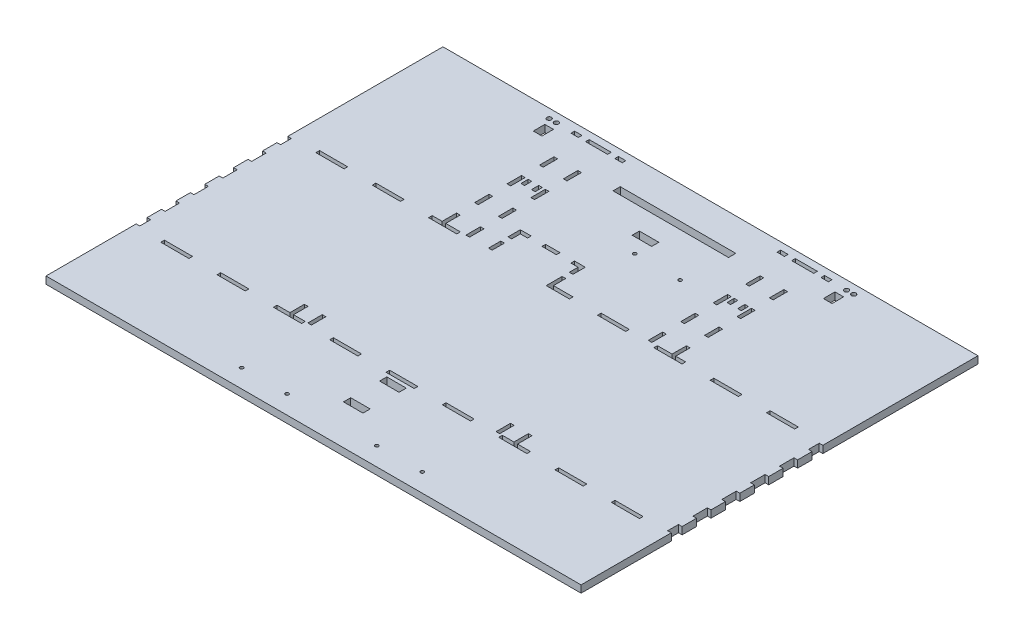
SolidWorks part; units mm, degrees
material "Acrylic (Medium-high impact)"
ref_plane "Front Plane" through (0, 0, 0) normal (0, 0, 1) x (1, 0, 0)
ref_plane "Top Plane" through (0, 0, 0) normal (0, 1, 0) x (1, 0, 0)
ref_plane "Right Plane" through (0, 0, 0) normal (1, 0, 0) x (0, 0, -1)
sketch "Sketch1" plane through (0, 0, 0) normal (0, 1, 0) x (1, 0, 0)
  line L1 (-235.3945, 69.85) -> (235.3945, 69.85)
  line L2 (-235.3945, 69.85) -> (-235.3945, -69.85)
  line L3 (-235.3945, -69.85) -> (235.3945, -69.85)
  line L4 (235.3945, 69.85) -> (235.3945, -69.85)
  point P4 (-235.3945, 0)
  point P6 (0, 69.85)
  dimension "D1" = 139.7
  dimension "D2" = 470.789
extrude "Boss-Extrude1" add sketch "Sketch1" along normal blind 6.35
sketch "Sketch2" plane through (0, 6.35, 0) normal (0, 1, 0) x (1, 0, 0)
  line L0 (235.3945, -69.85) -> (235.3945, 69.85) construction
  line L1 (-235.3945, 69.85) -> (235.3945, 69.85)
  line L2 (-235.3945, 69.85) -> (-235.3945, -69.85)
  line L3 (-235.3945, -69.85) -> (235.3945, -69.85)
  line L4 (235.3945, 69.85) -> (235.3945, -69.85)
  line L5 (-235.3945, -69.85) -> (235.3945, -69.85) construction
  line L7 (-232.2195, 66.675) -> (232.2195, 66.675)
  line L8 (-232.2195, 66.675) -> (-232.2195, -66.675)
  line L9 (-232.2195, -66.675) -> (232.2195, -66.675)
  line L10 (232.2195, 66.675) -> (232.2195, -66.675)
  point P7 (-232.2195, 0)
  point P14 (-235.3945, 0)
  point P15 (0, -66.675)
  point P16 (0, -69.85)
  point P17 (232.2195, 0)
  point P18 (235.3945, 0)
  dimension "D1" = 3.175
  dimension "D2" = 3.175
extrude "Boss-Extrude2" add sketch "Sketch2" along normal blind 298.45
sketch "Sketch3" plane through (0, 0, 69.85) normal (0, 0, 1) x (1, 0, 0)
  line L0 (73.4695, 304.8) -> (73.4695, 0) construction
  line L2 (-232.2195, 6.35) -> (232.2195, 6.35) construction
  line L4 (70.1675, 292.354) -> (70.1675, 6.35)
  line L5 (70.1675, 6.35) -> (76.7715, 6.35)
  line L6 (76.7715, 283.2407) -> (76.7715, 6.35)
  line L11 (76.7715, 101.6) -> (63.0555, 101.6) construction
  line L12 (-235.3945, 0) -> (235.3945, 0) construction
  line L13 (60.2615, 88.9) -> (60.2615, 101.6) construction
  line L14 (57.4675, 88.9) -> (63.0555, 88.9)
  line L15 (57.4675, 88.9) -> (57.4675, 71.9667)
  line L16 (57.4675, 71.9667) -> (63.0555, 71.9667)
  line L17 (63.0555, 88.9) -> (63.0555, 71.9667)
  line L18 (57.4675, 42.3333) -> (63.0555, 42.3333)
  line L19 (57.4675, 42.3333) -> (57.4675, 59.2667)
  line L20 (57.4675, 59.2667) -> (63.0555, 59.2667)
  line L21 (63.0555, 42.3333) -> (63.0555, 59.2667)
  line L26 (57.4675, 29.6333) -> (63.0555, 29.6333)
  line L27 (57.4675, 29.6333) -> (57.4675, 12.7)
  line L28 (57.4675, 12.7) -> (63.0555, 12.7)
  line L29 (63.0555, 29.6333) -> (63.0555, 12.7)
  line L30 (60.2615, 59.2667) -> (60.2615, 71.9667) construction
  line L31 (60.2615, 29.6333) -> (60.2615, 42.3333) construction
  line L32 (60.2615, 12.7) -> (60.2615, 0) construction
  line L33 (-235.3945, 304.8) -> (235.3945, 304.8) construction
  line L34 (-76.7715, 283.2407) -> (-76.7715, 6.35)
  line L35 (-76.7715, 6.35) -> (-70.1675, 6.35)
  line L36 (-70.1675, 292.354) -> (-70.1675, 6.35)
  line L37 (-70.1675, 292.354) -> (-89.7255, 292.354)
  line L38 (-79.3115, 285.7807) -> (-89.7255, 285.7807)
  line L39 (-89.7255, 292.354) -> (-89.7255, 285.7807)
  line L40 (-70.1675, 101.6) -> (-57.4675, 101.6) construction
  line L41 (-60.2615, 88.9) -> (-60.2615, 101.6) construction
  line L42 (-63.0555, 88.9) -> (-57.4675, 88.9)
  line L43 (-63.0555, 88.9) -> (-63.0555, 71.9667)
  line L44 (-63.0555, 71.9667) -> (-57.4675, 71.9667)
  line L45 (-57.4675, 88.9) -> (-57.4675, 71.9667)
  line L46 (-63.0555, 42.3333) -> (-57.4675, 42.3333)
  line L47 (-63.0555, 42.3333) -> (-63.0555, 59.2667)
  line L48 (-63.0555, 59.2667) -> (-57.4675, 59.2667)
  line L49 (-57.4675, 42.3333) -> (-57.4675, 59.2667)
  line L50 (-63.0555, 29.6333) -> (-57.4675, 29.6333)
  line L51 (-63.0555, 29.6333) -> (-63.0555, 12.7)
  line L52 (-63.0555, 12.7) -> (-57.4675, 12.7)
  line L53 (-57.4675, 29.6333) -> (-57.4675, 12.7)
  line L54 (-60.2615, 59.2667) -> (-60.2615, 71.9667) construction
  line L55 (-60.2615, 29.6333) -> (-60.2615, 42.3333) construction
  line L56 (-60.2615, 12.7) -> (-60.2615, 0) construction
  line L58 (70.1675, 292.354) -> (89.7255, 292.354)
  line L59 (89.7255, 292.354) -> (89.7255, 285.7807)
  line L60 (79.3115, 285.7807) -> (89.7255, 285.7807)
  line L61 (-235.3945, 304.8) -> (-235.3945, 0) construction
  line L62 (235.3945, 304.8) -> (235.3945, 0) construction
  arc A1 (-76.7715, 283.2407) -> (-79.3115, 285.7807) centre (-79.3115, 283.2407) ccw
  arc A2 (79.3115, 285.7807) -> (76.7715, 283.2407) centre (79.3115, 283.2407) ccw
  point P5 (73.4695, 6.35)
  dimension "D14" = 2.54
  dimension "D1" = 6.604
  dimension "D2" = 6.5733
  dimension "D3" = 158.623
  dimension "D4" = 158.623
  dimension "D6" = 101.6
  dimension "D7" = 12.7
  dimension "D8" = 12.7
  dimension "D9" = 5.588
  dimension "D11" = 6.604
  dimension "D12" = 12.954
  dimension "D13" = 286.004
  dimension "D15" = 12.7
  dimension "D16" = 12.7
  dimension "D17" = 5.588
extrude "Door Slot" cut sketch "Sketch3" against normal blind 12.7
sketch "Sketch4" plane through (0, 0, -66.675) normal (0, 0, 1) x (1, 0, 0)
  line L0 (-235.3945, 304.8) -> (235.3945, 304.8) construction
  line L1 (63.8175, 304.8) -> (70.1675, 304.8)
  line L2 (63.8175, 304.8) -> (63.8175, 6.35)
  line L3 (63.8175, 6.35) -> (70.1675, 6.35)
  line L4 (70.1675, 304.8) -> (70.1675, 6.35)
  line L5 (92.9005, 263.525) -> (92.9005, 247.65) construction
  line L7 (89.7255, 304.8) -> (96.0755, 304.8)
  line L8 (89.7255, 304.8) -> (89.7255, 6.35)
  line L9 (89.7255, 6.35) -> (96.0755, 6.35)
  line L10 (96.0755, 304.8) -> (96.0755, 6.35)
  line L11 (232.2195, 6.35) -> (-232.2195, 6.35) construction
  line L13 (70.1675, 304.8) -> (63.8175, 304.8)
  line L14 (70.1675, 304.8) -> (70.1675, 292.1)
  line L15 (70.1675, 292.1) -> (63.8175, 292.1)
  line L16 (63.8175, 304.8) -> (63.8175, 292.1)
  line L17 (70.1675, 276.225) -> (63.8175, 276.225)
  line L18 (70.1675, 276.225) -> (70.1675, 263.525)
  line L19 (70.1675, 263.525) -> (63.8175, 263.525)
  line L20 (63.8175, 276.225) -> (63.8175, 263.525)
  line L21 (63.8175, 6.35) -> (70.1675, 6.35)
  line L22 (63.8175, 6.35) -> (63.8175, 19.05)
  line L23 (63.8175, 19.05) -> (70.1675, 19.05)
  line L24 (70.1675, 6.35) -> (70.1675, 19.05)
  line L25 (63.8175, 34.925) -> (70.1675, 34.925)
  line L26 (63.8175, 34.925) -> (63.8175, 47.625)
  line L27 (63.8175, 47.625) -> (70.1675, 47.625)
  line L28 (70.1675, 34.925) -> (70.1675, 47.625)
  line L29 (63.8175, 92.075) -> (70.1675, 92.075)
  line L30 (63.8175, 92.075) -> (63.8175, 104.775)
  line L31 (63.8175, 104.775) -> (70.1675, 104.775)
  line L32 (70.1675, 92.075) -> (70.1675, 104.775)
  line L33 (63.8175, 149.225) -> (70.1675, 149.225)
  line L34 (63.8175, 149.225) -> (63.8175, 161.925)
  line L35 (63.8175, 161.925) -> (70.1675, 161.925)
  line L36 (70.1675, 149.225) -> (70.1675, 161.925)
  line L37 (63.8175, 177.8) -> (70.1675, 177.8)
  line L38 (63.8175, 177.8) -> (63.8175, 190.5)
  line L39 (63.8175, 190.5) -> (70.1675, 190.5)
  line L40 (70.1675, 177.8) -> (70.1675, 190.5)
  line L41 (63.8175, 206.375) -> (70.1675, 206.375)
  line L42 (63.8175, 206.375) -> (63.8175, 219.075)
  line L43 (63.8175, 219.075) -> (70.1675, 219.075)
  line L44 (70.1675, 206.375) -> (70.1675, 219.075)
  line L45 (63.8175, 234.95) -> (70.1675, 234.95)
  line L46 (63.8175, 234.95) -> (63.8175, 247.65)
  line L47 (63.8175, 247.65) -> (70.1675, 247.65)
  line L48 (70.1675, 234.95) -> (70.1675, 247.65)
  line L49 (70.1675, 133.35) -> (63.8175, 133.35)
  line L50 (70.1675, 133.35) -> (70.1675, 120.65)
  line L51 (70.1675, 120.65) -> (63.8175, 120.65)
  line L52 (63.8175, 133.35) -> (63.8175, 120.65)
  line L53 (70.1675, 76.2) -> (63.8175, 76.2)
  line L54 (70.1675, 76.2) -> (70.1675, 63.5)
  line L55 (70.1675, 63.5) -> (63.8175, 63.5)
  line L56 (63.8175, 76.2) -> (63.8175, 63.5)
  line L57 (66.9925, 304.8) -> (66.9925, 292.1) construction
  line L58 (66.9925, 292.1) -> (66.9925, 276.225) construction
  line L59 (66.9925, 276.225) -> (66.9925, 263.525) construction
  line L60 (66.9925, 247.65) -> (66.9925, 234.95) construction
  line L61 (66.9925, 234.95) -> (66.9925, 219.075) construction
  line L62 (66.9925, 219.075) -> (66.9925, 206.375) construction
  line L63 (66.9925, 206.375) -> (66.9925, 190.5) construction
  line L64 (66.9925, 190.5) -> (66.9925, 177.8) construction
  line L65 (66.9925, 177.8) -> (66.9925, 161.925) construction
  line L66 (66.9925, 161.925) -> (66.9925, 149.225) construction
  line L67 (66.9925, 133.35) -> (66.9925, 120.65) construction
  line L68 (66.9925, 120.65) -> (66.9925, 104.775) construction
  line L69 (66.9925, 104.775) -> (66.9925, 92.075) construction
  line L70 (66.9925, 92.075) -> (66.9925, 76.2) construction
  line L71 (66.9925, 76.2) -> (66.9925, 63.5) construction
  line L72 (66.9925, 63.5) -> (66.9925, 47.625) construction
  line L73 (66.9925, 47.625) -> (66.9925, 34.925) construction
  line L74 (66.9925, 34.925) -> (66.9925, 19.05) construction
  line L75 (66.9925, 19.05) -> (66.9925, 6.35) construction
  line L76 (66.9925, 149.225) -> (66.9925, 133.35) construction
  line L77 (66.9925, 263.525) -> (66.9925, 247.65) construction
  line L78 (79.9465, 304.8) -> (79.9465, 0) construction
  line L79 (235.3945, 304.8) -> (-235.3945, 304.8) construction
  line L80 (235.3945, 0) -> (-235.3945, 0) construction
  line L81 (79.9465, 15.1854) -> (89.7255, 15.1854) construction
  line L82 (79.9465, 15.1854) -> (70.1675, 15.1854) construction
  line L83 (92.9005, 149.225) -> (92.9005, 133.35) construction
  line L84 (92.9005, 19.05) -> (92.9005, 6.35) construction
  line L85 (92.9005, 34.925) -> (92.9005, 19.05) construction
  line L86 (92.9005, 47.625) -> (92.9005, 34.925) construction
  line L87 (92.9005, 63.5) -> (92.9005, 47.625) construction
  line L88 (92.9005, 76.2) -> (92.9005, 63.5) construction
  line L89 (92.9005, 92.075) -> (92.9005, 76.2) construction
  line L90 (92.9005, 104.775) -> (92.9005, 92.075) construction
  line L91 (92.9005, 120.65) -> (92.9005, 104.775) construction
  line L92 (92.9005, 133.35) -> (92.9005, 120.65) construction
  line L93 (92.9005, 161.925) -> (92.9005, 149.225) construction
  line L94 (92.9005, 177.8) -> (92.9005, 161.925) construction
  line L95 (92.9005, 190.5) -> (92.9005, 177.8) construction
  line L96 (92.9005, 206.375) -> (92.9005, 190.5) construction
  line L97 (92.9005, 219.075) -> (92.9005, 206.375) construction
  line L98 (92.9005, 234.95) -> (92.9005, 219.075) construction
  line L99 (92.9005, 247.65) -> (92.9005, 234.95) construction
  line L100 (92.9005, 276.225) -> (92.9005, 263.525) construction
  line L101 (92.9005, 292.1) -> (92.9005, 276.225) construction
  line L102 (92.9005, 304.8) -> (92.9005, 292.1) construction
  line L103 (96.0755, 76.2) -> (96.0755, 63.5)
  line L104 (89.7255, 63.5) -> (96.0755, 63.5)
  line L105 (89.7255, 76.2) -> (89.7255, 63.5)
  line L106 (89.7255, 76.2) -> (96.0755, 76.2)
  line L107 (96.0755, 133.35) -> (96.0755, 120.65)
  line L108 (89.7255, 120.65) -> (96.0755, 120.65)
  line L109 (89.7255, 133.35) -> (89.7255, 120.65)
  line L110 (89.7255, 133.35) -> (96.0755, 133.35)
  line L111 (89.7255, 234.95) -> (89.7255, 247.65)
  line L112 (96.0755, 247.65) -> (89.7255, 247.65)
  line L113 (96.0755, 234.95) -> (96.0755, 247.65)
  line L114 (96.0755, 234.95) -> (89.7255, 234.95)
  line L115 (89.7255, 206.375) -> (89.7255, 219.075)
  line L116 (96.0755, 219.075) -> (89.7255, 219.075)
  line L117 (96.0755, 206.375) -> (96.0755, 219.075)
  line L118 (96.0755, 206.375) -> (89.7255, 206.375)
  line L119 (89.7255, 177.8) -> (89.7255, 190.5)
  line L120 (96.0755, 190.5) -> (89.7255, 190.5)
  line L121 (96.0755, 177.8) -> (96.0755, 190.5)
  line L122 (96.0755, 177.8) -> (89.7255, 177.8)
  line L123 (89.7255, 149.225) -> (89.7255, 161.925)
  line L124 (96.0755, 161.925) -> (89.7255, 161.925)
  line L125 (96.0755, 149.225) -> (96.0755, 161.925)
  line L126 (96.0755, 149.225) -> (89.7255, 149.225)
  line L127 (89.7255, 92.075) -> (89.7255, 104.775)
  line L128 (96.0755, 104.775) -> (89.7255, 104.775)
  line L129 (96.0755, 92.075) -> (96.0755, 104.775)
  line L130 (96.0755, 92.075) -> (89.7255, 92.075)
  line L131 (89.7255, 34.925) -> (89.7255, 47.625)
  line L132 (96.0755, 47.625) -> (89.7255, 47.625)
  line L133 (96.0755, 34.925) -> (96.0755, 47.625)
  line L134 (96.0755, 34.925) -> (89.7255, 34.925)
  line L135 (89.7255, 6.35) -> (89.7255, 19.05)
  line L136 (96.0755, 19.05) -> (89.7255, 19.05)
  line L137 (96.0755, 6.35) -> (96.0755, 19.05)
  line L138 (96.0755, 6.35) -> (89.7255, 6.35)
  line L139 (96.0755, 276.225) -> (96.0755, 263.525)
  line L140 (89.7255, 263.525) -> (96.0755, 263.525)
  line L141 (89.7255, 276.225) -> (89.7255, 263.525)
  line L142 (89.7255, 276.225) -> (96.0755, 276.225)
  line L143 (96.0755, 304.8) -> (96.0755, 292.1)
  line L144 (89.7255, 292.1) -> (96.0755, 292.1)
  line L145 (89.7255, 304.8) -> (89.7255, 292.1)
  line L146 (89.7255, 304.8) -> (96.0755, 304.8)
  line L147 (89.7255, 304.8) -> (89.7255, 6.35)
  line L148 (96.0755, 6.35) -> (89.7255, 6.35)
  line L149 (96.0755, 304.8) -> (96.0755, 6.35)
  line L150 (96.0755, 304.8) -> (89.7255, 304.8)
  line L151 (-96.0755, 304.8) -> (-89.7255, 304.8)
  line L152 (-96.0755, 304.8) -> (-96.0755, 6.35)
  line L153 (-96.0755, 6.35) -> (-89.7255, 6.35)
  line L154 (-89.7255, 304.8) -> (-89.7255, 6.35)
  line L155 (-66.9925, 263.525) -> (-66.9925, 247.65) construction
  line L156 (-70.1675, 304.8) -> (-63.8175, 304.8)
  line L157 (-70.1675, 304.8) -> (-70.1675, 6.35)
  line L158 (-70.1675, 6.35) -> (-63.8175, 6.35)
  line L159 (-63.8175, 304.8) -> (-63.8175, 6.35)
  line L160 (-89.7255, 304.8) -> (-96.0755, 304.8)
  line L161 (-89.7255, 304.8) -> (-89.7255, 292.1)
  line L162 (-89.7255, 292.1) -> (-96.0755, 292.1)
  line L163 (-96.0755, 304.8) -> (-96.0755, 292.1)
  line L164 (-89.7255, 276.225) -> (-96.0755, 276.225)
  line L165 (-89.7255, 276.225) -> (-89.7255, 263.525)
  line L166 (-89.7255, 263.525) -> (-96.0755, 263.525)
  line L167 (-96.0755, 276.225) -> (-96.0755, 263.525)
  line L168 (-96.0755, 6.35) -> (-89.7255, 6.35)
  line L169 (-96.0755, 6.35) -> (-96.0755, 19.05)
  line L170 (-96.0755, 19.05) -> (-89.7255, 19.05)
  line L171 (-89.7255, 6.35) -> (-89.7255, 19.05)
  line L172 (-96.0755, 34.925) -> (-89.7255, 34.925)
  line L173 (-96.0755, 34.925) -> (-96.0755, 47.625)
  line L174 (-96.0755, 47.625) -> (-89.7255, 47.625)
  line L175 (-89.7255, 34.925) -> (-89.7255, 47.625)
  line L176 (-96.0755, 92.075) -> (-89.7255, 92.075)
  line L177 (-96.0755, 92.075) -> (-96.0755, 104.775)
  line L178 (-96.0755, 104.775) -> (-89.7255, 104.775)
  line L179 (-89.7255, 92.075) -> (-89.7255, 104.775)
  line L180 (-96.0755, 149.225) -> (-89.7255, 149.225)
  line L181 (-96.0755, 149.225) -> (-96.0755, 161.925)
  line L182 (-96.0755, 161.925) -> (-89.7255, 161.925)
  line L183 (-89.7255, 149.225) -> (-89.7255, 161.925)
  line L184 (-96.0755, 177.8) -> (-89.7255, 177.8)
  line L185 (-96.0755, 177.8) -> (-96.0755, 190.5)
  line L186 (-96.0755, 190.5) -> (-89.7255, 190.5)
  line L187 (-89.7255, 177.8) -> (-89.7255, 190.5)
  line L188 (-96.0755, 206.375) -> (-89.7255, 206.375)
  line L189 (-96.0755, 206.375) -> (-96.0755, 219.075)
  line L190 (-96.0755, 219.075) -> (-89.7255, 219.075)
  line L191 (-89.7255, 206.375) -> (-89.7255, 219.075)
  line L192 (-96.0755, 234.95) -> (-89.7255, 234.95)
  line L193 (-96.0755, 234.95) -> (-96.0755, 247.65)
  line L194 (-96.0755, 247.65) -> (-89.7255, 247.65)
  line L195 (-89.7255, 234.95) -> (-89.7255, 247.65)
  line L196 (-89.7255, 133.35) -> (-96.0755, 133.35)
  line L197 (-89.7255, 133.35) -> (-89.7255, 120.65)
  line L198 (-89.7255, 120.65) -> (-96.0755, 120.65)
  line L199 (-96.0755, 133.35) -> (-96.0755, 120.65)
  line L200 (-89.7255, 76.2) -> (-96.0755, 76.2)
  line L201 (-89.7255, 76.2) -> (-89.7255, 63.5)
  line L202 (-89.7255, 63.5) -> (-96.0755, 63.5)
  line L203 (-96.0755, 76.2) -> (-96.0755, 63.5)
  line L204 (-92.9005, 304.8) -> (-92.9005, 292.1) construction
  line L205 (-92.9005, 292.1) -> (-92.9005, 276.225) construction
  line L206 (-92.9005, 276.225) -> (-92.9005, 263.525) construction
  line L207 (-92.9005, 247.65) -> (-92.9005, 234.95) construction
  line L208 (-92.9005, 234.95) -> (-92.9005, 219.075) construction
  line L209 (-92.9005, 219.075) -> (-92.9005, 206.375) construction
  line L210 (-92.9005, 206.375) -> (-92.9005, 190.5) construction
  line L211 (-92.9005, 190.5) -> (-92.9005, 177.8) construction
  line L212 (-92.9005, 177.8) -> (-92.9005, 161.925) construction
  line L213 (-92.9005, 161.925) -> (-92.9005, 149.225) construction
  line L214 (-92.9005, 133.35) -> (-92.9005, 120.65) construction
  line L215 (-92.9005, 120.65) -> (-92.9005, 104.775) construction
  line L216 (-92.9005, 104.775) -> (-92.9005, 92.075) construction
  line L217 (-92.9005, 92.075) -> (-92.9005, 76.2) construction
  line L218 (-92.9005, 76.2) -> (-92.9005, 63.5) construction
  line L219 (-92.9005, 63.5) -> (-92.9005, 47.625) construction
  line L220 (-92.9005, 47.625) -> (-92.9005, 34.925) construction
  line L221 (-92.9005, 34.925) -> (-92.9005, 19.05) construction
  line L222 (-92.9005, 19.05) -> (-92.9005, 6.35) construction
  line L223 (-92.9005, 149.225) -> (-92.9005, 133.35) construction
  line L224 (-92.9005, 263.525) -> (-92.9005, 247.65) construction
  line L225 (-79.9465, 304.8) -> (-79.9465, 0) construction
  line L226 (-79.9465, 341.727) -> (-70.1675, 341.727) construction
  line L227 (-79.9465, 341.727) -> (-89.7255, 341.727) construction
  line L228 (-66.9925, 149.225) -> (-66.9925, 133.35) construction
  line L229 (-66.9925, 19.05) -> (-66.9925, 6.35) construction
  line L230 (-66.9925, 34.925) -> (-66.9925, 19.05) construction
  line L231 (-66.9925, 47.625) -> (-66.9925, 34.925) construction
  line L232 (-66.9925, 63.5) -> (-66.9925, 47.625) construction
  line L233 (-66.9925, 76.2) -> (-66.9925, 63.5) construction
  line L234 (-66.9925, 92.075) -> (-66.9925, 76.2) construction
  line L235 (-66.9925, 104.775) -> (-66.9925, 92.075) construction
  line L236 (-66.9925, 120.65) -> (-66.9925, 104.775) construction
  line L237 (-66.9925, 133.35) -> (-66.9925, 120.65) construction
  line L238 (-66.9925, 161.925) -> (-66.9925, 149.225) construction
  line L239 (-66.9925, 177.8) -> (-66.9925, 161.925) construction
  line L240 (-66.9925, 190.5) -> (-66.9925, 177.8) construction
  line L241 (-66.9925, 206.375) -> (-66.9925, 190.5) construction
  line L242 (-66.9925, 219.075) -> (-66.9925, 206.375) construction
  line L243 (-66.9925, 234.95) -> (-66.9925, 219.075) construction
  line L244 (-66.9925, 247.65) -> (-66.9925, 234.95) construction
  line L245 (-66.9925, 276.225) -> (-66.9925, 263.525) construction
  line L246 (-66.9925, 292.1) -> (-66.9925, 276.225) construction
  line L247 (-66.9925, 304.8) -> (-66.9925, 292.1) construction
  line L248 (-63.8175, 76.2) -> (-63.8175, 63.5)
  line L249 (-70.1675, 63.5) -> (-63.8175, 63.5)
  line L250 (-70.1675, 76.2) -> (-70.1675, 63.5)
  line L251 (-70.1675, 76.2) -> (-63.8175, 76.2)
  line L252 (-63.8175, 133.35) -> (-63.8175, 120.65)
  line L253 (-70.1675, 120.65) -> (-63.8175, 120.65)
  line L254 (-70.1675, 133.35) -> (-70.1675, 120.65)
  line L255 (-70.1675, 133.35) -> (-63.8175, 133.35)
  line L256 (-70.1675, 234.95) -> (-70.1675, 247.65)
  line L257 (-63.8175, 247.65) -> (-70.1675, 247.65)
  line L258 (-63.8175, 234.95) -> (-63.8175, 247.65)
  line L259 (-63.8175, 234.95) -> (-70.1675, 234.95)
  line L260 (-70.1675, 206.375) -> (-70.1675, 219.075)
  line L261 (-63.8175, 219.075) -> (-70.1675, 219.075)
  line L262 (-63.8175, 206.375) -> (-63.8175, 219.075)
  line L263 (-63.8175, 206.375) -> (-70.1675, 206.375)
  line L264 (-70.1675, 177.8) -> (-70.1675, 190.5)
  line L265 (-63.8175, 190.5) -> (-70.1675, 190.5)
  line L266 (-63.8175, 177.8) -> (-63.8175, 190.5)
  line L267 (-63.8175, 177.8) -> (-70.1675, 177.8)
  line L268 (-70.1675, 149.225) -> (-70.1675, 161.925)
  line L269 (-63.8175, 161.925) -> (-70.1675, 161.925)
  line L270 (-63.8175, 149.225) -> (-63.8175, 161.925)
  line L271 (-63.8175, 149.225) -> (-70.1675, 149.225)
  line L272 (-70.1675, 92.075) -> (-70.1675, 104.775)
  line L273 (-63.8175, 104.775) -> (-70.1675, 104.775)
  line L274 (-63.8175, 92.075) -> (-63.8175, 104.775)
  line L275 (-63.8175, 92.075) -> (-70.1675, 92.075)
  line L276 (-70.1675, 34.925) -> (-70.1675, 47.625)
  line L277 (-63.8175, 47.625) -> (-70.1675, 47.625)
  line L278 (-63.8175, 34.925) -> (-63.8175, 47.625)
  line L279 (-63.8175, 34.925) -> (-70.1675, 34.925)
  line L280 (-70.1675, 6.35) -> (-70.1675, 19.05)
  line L281 (-63.8175, 19.05) -> (-70.1675, 19.05)
  line L282 (-63.8175, 6.35) -> (-63.8175, 19.05)
  line L283 (-63.8175, 6.35) -> (-70.1675, 6.35)
  line L284 (-63.8175, 276.225) -> (-63.8175, 263.525)
  line L285 (-70.1675, 263.525) -> (-63.8175, 263.525)
  line L286 (-70.1675, 276.225) -> (-70.1675, 263.525)
  line L287 (-70.1675, 276.225) -> (-63.8175, 276.225)
  line L288 (-63.8175, 304.8) -> (-63.8175, 292.1)
  line L289 (-70.1675, 292.1) -> (-63.8175, 292.1)
  line L290 (-70.1675, 304.8) -> (-70.1675, 292.1)
  line L291 (-70.1675, 304.8) -> (-63.8175, 304.8)
  line L292 (-70.1675, 304.8) -> (-70.1675, 6.35)
  line L293 (-63.8175, 6.35) -> (-70.1675, 6.35)
  line L294 (-63.8175, 304.8) -> (-63.8175, 6.35)
  line L295 (-63.8175, 304.8) -> (-70.1675, 304.8)
  line L296 (-235.3945, 0) -> (235.3945, 0) construction
  line L297 (-89.7255, 292.354) -> (-89.7255, 285.7807) construction
  line L298 (-70.1675, 6.35) -> (-70.1675, 292.354) construction
  line L299 (70.1675, 292.354) -> (70.1675, 6.35) construction
  line L300 (89.7255, 285.7807) -> (89.7255, 292.354) construction
  dimension "D1" = 6.35
  dimension "D2" = 12.7
  dimension "D3" = 6.35
  dimension "D4" = 12.7
extrude "Door Guide Holes" cut sketch "Sketch4" against normal up to next (3.175 mm away) contours L2 L47 L4 L19 | L45 L2 L43 L4 | L41 L2 L39 L4 | L37 L2 L35 L4 | L49 L4 L33 L2 | L4 L51 L2 L31 | L53 L4 L29 L2 | L4 L55 L2 L27 | L25 L2 L23 L4 | L164 L154 L162 L152 | L152 L194 L154 L166 | L192 L152 L190 L154 | L188 L152 L186 L154 | L184 L152 L182 L154 | L196 L154 L180 L152 | L154 L198 L152 L178 | L200 L154 L176 L152 | L154 L202 L152 L174 | L172 L152 L170 L154 | L144 L8 L142 L10 | L140 L8 L112 L10 | L116 L10 L114 L8 | L120 L10 L118 L8 | L124 L10 L122 L8 | L10 L126 L8 L110 | L128 L10 L108 L8 | L10 L130 L8 L106 | L132 L10 L104 L8 | L136 L10 L134 L8 | L289 L157 L287 L159 | L285 L157 L257 L159 | L261 L159 L259 L157 | L265 L159 L263 L157 | L269 L159 L267 L157 | L159 L271 L157 L255 | L273 L159 L253 L157 | L159 L275 L157 L251 | L277 L159 L249 L157 | L281 L159 L279 L157 | L17 L4 L15 L2 region at (66.9925, 284.1625, -66.675) region at (66.9925, 255.5875, -66.675) region at (66.9925, 227.0125, -66.675) region at (66.9925, 198.4375, -66.675) region at (66.9925, 169.8625, -66.675) region at (66.9925, 141.2875, -66.675) region at (66.9925, 112.7125, -66.675) region at (66.9925, 84.1375, -66.675) region at (66.9925, 55.5625, -66.675) region at (66.9925, 26.9875, -66.675) region at (92.9005, 284.1625, -66.675) region at (92.9005, 255.5875, -66.675) region at (92.9005, 227.0125, -66.675) region at (92.9005, 198.4375, -66.675) region at (92.9005, 169.8625, -66.675) region at (92.9005, 141.2875, -66.675) region at (92.9005, 112.7125, -66.675) region at (92.9005, 84.1375, -66.675) region at (92.9005, 55.5625, -66.675) region at (92.9005, 26.9875, -66.675) region at (-92.9005, 284.1625, -66.675) region at (-92.9005, 255.5875, -66.675) region at (-92.9005, 227.0125, -66.675) region at (-92.9005, 198.4375, -66.675) region at (-92.9005, 169.8625, -66.675) region at (-92.9005, 141.2875, -66.675) region at (-92.9005, 112.7125, -66.675) region at (-92.9005, 84.1375, -66.675) region at (-92.9005, 55.5625, -66.675) region at (-92.9005, 26.9875, -66.675) region at (-66.9925, 284.1625, -66.675) region at (-66.9925, 255.5875, -66.675) region at (-66.9925, 227.0125, -66.675) region at (-66.9925, 198.4375, -66.675) region at (-66.9925, 169.8625, -66.675) region at (-66.9925, 141.2875, -66.675) region at (-66.9925, 112.7125, -66.675) region at (-66.9925, 84.1375, -66.675) region at (-66.9925, 55.5625, -66.675) region at (-66.9925, 26.9875, -66.675)
sketch "Lever Holes" plane through (0, 0, -69.85) normal (0, 0, 1) x (1, 0, 0)
  line L0 (-53.2675, 37.685) -> (-27.8675, 37.685)
  line L1 (-53.2675, 37.685) -> (-53.2675, 30.065)
  line L2 (-53.2675, 30.065) -> (-27.8675, 30.065)
  line L3 (-27.8675, 37.685) -> (-27.8675, 30.065)
  line L4 (-53.8175, 16.35) -> (-49.8175, 16.35)
  line L5 (-53.8175, 16.35) -> (-53.8175, 10)
  line L6 (-53.8175, 10) -> (-49.8175, 10)
  line L7 (-49.8175, 16.35) -> (-49.8175, 10)
  line L8 (-7.8175, 16.35) -> (-3.8175, 16.35)
  line L9 (-7.8175, 16.35) -> (-7.8175, 10)
  line L10 (-7.8175, 10) -> (-3.8175, 10)
  line L11 (-3.8175, 16.35) -> (-3.8175, 10)
  line L12 (-49.8175, 13.175) -> (-7.8175, 13.175) construction
  line L13 (76.7715, 6.35) -> (76.7715, 283.2407) construction
  line L14 (76.7715, 6.35) -> (232.2195, 6.35) construction
  line L15 (232.2195, 6.35) -> (-232.2195, 6.35) construction
  line L16 (216.3445, 160.275) -> (216.3445, 144.525) construction
  line L17 (235.3945, 304.8) -> (235.3945, 0) construction
  line L18 (0, -3.4925) -> (0, 3.4925) construction
  line L19 (76.7715, 154.6735) -> (-76.7715, 154.6735) construction
  line L20 (-76.7715, 283.2407) -> (-76.7715, 6.35) construction
  line L21 (0, 171.6172) -> (0, 142.0428) construction
  line L22 (7.8175, 16.35) -> (7.8175, 10)
  line L23 (7.8175, 10) -> (3.8175, 10)
  line L24 (3.8175, 16.35) -> (3.8175, 10)
  line L25 (7.8175, 16.35) -> (3.8175, 16.35)
  line L26 (53.2675, 37.685) -> (53.2675, 30.065)
  line L27 (53.2675, 30.065) -> (27.8675, 30.065)
  line L28 (27.8675, 37.685) -> (27.8675, 30.065)
  line L29 (53.2675, 37.685) -> (27.8675, 37.685)
  line L30 (53.8175, 16.35) -> (53.8175, 10)
  line L31 (53.8175, 10) -> (49.8175, 10)
  line L32 (49.8175, 16.35) -> (49.8175, 10)
  line L33 (53.8175, 16.35) -> (49.8175, 16.35)
  line L35 (63.8175, 19.05) -> (63.8175, 34.925) construction
  circle A0 centre (216.3445, 160.275) radius 1.5
  circle A1 centre (216.3445, 144.525) radius 1.5
  circle A2 centre (-216.3445, 160.275) radius 1.5
  circle A3 centre (-216.3445, 144.525) radius 1.5
  point P13 (-40.5675, 30.065)
  point P31 (216.3445, 152.4)
  point P32 (235.3945, 152.4)
  dimension "D10" = 3
  dimension "D1" = 25.4
  dimension "D2" = 7.62
  dimension "D3" = 4
  dimension "D4" = 6.35
  dimension "D5" = 42
  dimension "D6" = 31.335
  dimension "D7" = 10
  dimension "D8" = 10
  dimension "D9" = 13.25
  dimension "D11" = 15.75
  dimension "D12" = 19.05
extrude "LeverHole Cut" cut sketch "Lever Holes" along normal up to next
extrude "Lbracket Thru Holes" cut sketch "Lever Holes<2>" along normal through all contours A2 | A3 | A0 | A1 | A2 | A3 | A0 | A1 region at (216.3445, 160.275, -69.85) region at (216.3445, 144.525, -69.85) region at (-216.3445, 160.275, -69.85) region at (-216.3445, 144.525, -69.85)
sketch "Lever Holes<2>" plane through (0, 0, -69.85) normal (0, 0, 1) x (1, 0, 0) same geometry as "Lever Holes"
sketch "Sketch8" plane through (-235.3945, 0, 0) normal (-1, 0, 0) x (0, 0, 1)
  line L0 (-69.85, 0) -> (69.85, 0) construction
  circle A0 centre (0, 19.05) radius 3.175
  point P6 (0, 0)
  dimension "D1" = 6.35
  dimension "D2" = 19.05
extrude "Tether Hole" cut sketch "Sketch8" against normal through all
sketch "Sketch16" plane through (0, 0, 69.85) normal (0, 0, 1) x (1, 0, 0)
  line L0 (-235.3945, 304.8) -> (235.3945, 304.8) construction
  line L1 (57.3405, 304.8) -> (102.5525, 304.8)
  line L2 (57.3405, 304.8) -> (57.3405, 295.529)
  line L3 (57.3405, 295.529) -> (102.5525, 295.529)
  line L4 (102.5525, 304.8) -> (102.5525, 295.529)
  line L6 (47.8155, 295.529) -> (57.3405, 295.529)
  line L8 (57.3405, 295.529) -> (57.3405, 304.8)
  line L9 (57.3405, 304.8) -> (47.8155, 304.8)
  line L10 (47.8155, 295.529) -> (47.8155, 304.8)
  line L11 (102.5525, 295.529) -> (112.0775, 295.529)
  line L12 (102.5525, 295.529) -> (102.5525, 304.8)
  line L13 (102.5525, 304.8) -> (112.0775, 304.8)
  line L14 (112.0775, 295.529) -> (112.0775, 304.8)
  line L15 (89.7255, 292.354) -> (70.1675, 292.354) construction
  line L16 (-102.5525, 304.8) -> (-57.3405, 304.8)
  line L17 (-102.5525, 304.8) -> (-102.5525, 295.529)
  line L18 (-102.5525, 295.529) -> (-57.3405, 295.529)
  line L19 (-57.3405, 304.8) -> (-57.3405, 295.529)
  line L20 (-112.0775, 295.529) -> (-102.5525, 295.529)
  line L21 (-102.5525, 295.529) -> (-102.5525, 304.8)
  line L22 (-102.5525, 304.8) -> (-112.0775, 304.8)
  line L23 (-112.0775, 295.529) -> (-112.0775, 304.8)
  line L24 (-57.3405, 295.529) -> (-47.8155, 295.529)
  line L25 (-57.3405, 295.529) -> (-57.3405, 304.8)
  line L26 (-57.3405, 304.8) -> (-47.8155, 304.8)
  line L27 (-47.8155, 295.529) -> (-47.8155, 304.8)
  line L28 (-70.1675, 292.354) -> (-89.7255, 292.354) construction
  point P15 (79.9465, 292.354)
  point P16 (79.9465, 295.529)
  point P25 (-79.9465, 292.354)
  point P28 (-79.9465, 295.529)
  dimension "D1" = 45.212
  dimension "D2" = 3.175
  dimension "D3" = 9.525
  dimension "D4" = 45.212
  dimension "D5" = 9.525
extrude "Door Guide Roof Slots" cut sketch "Sketch16" against normal up to next contours L10 L6 L2 L9 | L11 L14 L13 L4 | L23 L20 L17 L22 | L24 L27 L26 L19 region at (52.578, 300.1645, 69.85) region at (107.315, 300.1645, 69.85) region at (-107.315, 300.1645, 69.85) region at (-52.578, 300.1645, 69.85)
sketch "Bottom" plane through (0, 0, 0) normal (0, -1, 0) x (1, 0, 0)
  line L0 (-232.2195, 66.675) -> (-112.0775, 66.675) construction
  line L1 (-235.3945, 69.85) -> (-210.6161, 69.85)
  line L2 (-235.3945, 69.85) -> (-235.3945, 66.675)
  line L3 (-235.3945, 66.675) -> (-210.6161, 66.675)
  line L4 (-210.6161, 69.85) -> (-210.6161, 66.675)
  line L5 (-210.6161, 69.85) -> (-185.8378, 69.85)
  line L6 (-210.6161, 69.85) -> (-210.6161, 66.675)
  line L7 (-210.6161, 66.675) -> (-185.8378, 66.675)
  line L8 (-185.8378, 69.85) -> (-185.8378, 66.675)
  line L9 (-185.8378, 69.85) -> (-161.0594, 69.85)
  line L10 (-185.8378, 69.85) -> (-185.8378, 66.675)
  line L11 (-185.8378, 66.675) -> (-161.0594, 66.675)
  line L12 (-161.0594, 69.85) -> (-161.0594, 66.675)
  line L13 (-161.0594, 69.85) -> (-136.281, 69.85)
  line L14 (-161.0594, 69.85) -> (-161.0594, 66.675)
  line L15 (-161.0594, 66.675) -> (-136.281, 66.675)
  line L16 (-136.281, 69.85) -> (-136.281, 66.675)
  line L17 (-235.3945, 69.85) -> (235.3945, 69.85) construction
  line L19 (-136.281, 69.85) -> (-111.5027, 69.85)
  line L20 (-136.281, 69.85) -> (-136.281, 66.675)
  line L21 (-136.281, 66.675) -> (-111.5027, 66.675)
  line L22 (-111.5027, 69.85) -> (-111.5027, 66.675)
  line L23 (-111.5027, 69.85) -> (-86.7243, 69.85)
  line L24 (-111.5027, 69.85) -> (-111.5027, 66.675)
  line L25 (-111.5027, 66.675) -> (-86.7243, 66.675)
  line L26 (-86.7243, 69.85) -> (-86.7243, 66.675)
  line L27 (-86.7243, 69.85) -> (-61.9459, 69.85)
  line L28 (-86.7243, 69.85) -> (-86.7243, 66.675)
  line L29 (-86.7243, 66.675) -> (-61.9459, 66.675)
  line L30 (-61.9459, 69.85) -> (-61.9459, 66.675)
  line L31 (-61.9459, 69.85) -> (-37.1676, 69.85)
  line L32 (-61.9459, 69.85) -> (-61.9459, 66.675)
  line L33 (-61.9459, 66.675) -> (-37.1676, 66.675)
  line L34 (-37.1676, 69.85) -> (-37.1676, 66.675)
  line L36 (-37.1676, 69.85) -> (-12.3892, 69.85)
  line L37 (-37.1676, 69.85) -> (-37.1676, 66.675)
  line L38 (-37.1676, 66.675) -> (-12.3892, 66.675)
  line L39 (-12.3892, 69.85) -> (-12.3892, 66.675)
  line L40 (-12.3892, 69.85) -> (12.3892, 69.85)
  line L41 (-12.3892, 69.85) -> (-12.3892, 66.675)
  line L42 (-12.3892, 66.675) -> (12.3892, 66.675)
  line L43 (12.3892, 69.85) -> (12.3892, 66.675)
  line L44 (12.3892, 69.85) -> (37.1676, 69.85)
  line L45 (12.3892, 69.85) -> (12.3892, 66.675)
  line L46 (12.3892, 66.675) -> (37.1676, 66.675)
  line L47 (37.1676, 69.85) -> (37.1676, 66.675)
  line L48 (37.1676, 69.85) -> (61.9459, 69.85)
  line L49 (37.1676, 69.85) -> (37.1676, 66.675)
  line L50 (37.1676, 66.675) -> (61.9459, 66.675)
  line L51 (61.9459, 69.85) -> (61.9459, 66.675)
  line L52 (61.9459, 69.85) -> (86.7243, 69.85)
  line L53 (61.9459, 69.85) -> (61.9459, 66.675)
  line L54 (61.9459, 66.675) -> (86.7243, 66.675)
  line L55 (86.7243, 69.85) -> (86.7243, 66.675)
  line L56 (86.7243, 69.85) -> (111.5027, 69.85)
  line L57 (86.7243, 69.85) -> (86.7243, 66.675)
  line L58 (86.7243, 66.675) -> (111.5027, 66.675)
  line L59 (111.5027, 69.85) -> (111.5027, 66.675)
  line L60 (111.5027, 69.85) -> (136.281, 69.85)
  line L61 (111.5027, 69.85) -> (111.5027, 66.675)
  line L62 (111.5027, 66.675) -> (136.281, 66.675)
  line L63 (136.281, 69.85) -> (136.281, 66.675)
  line L64 (136.281, 69.85) -> (161.0594, 69.85)
  line L65 (136.281, 69.85) -> (136.281, 66.675)
  line L66 (136.281, 66.675) -> (161.0594, 66.675)
  line L67 (161.0594, 69.85) -> (161.0594, 66.675)
  line L68 (161.0594, 69.85) -> (185.8378, 69.85)
  line L69 (161.0594, 69.85) -> (161.0594, 66.675)
  line L70 (161.0594, 66.675) -> (185.8378, 66.675)
  line L71 (185.8378, 69.85) -> (185.8378, 66.675)
  line L72 (185.8378, 69.85) -> (210.6161, 69.85)
  line L73 (185.8378, 69.85) -> (185.8378, 66.675)
  line L74 (185.8378, 66.675) -> (210.6161, 66.675)
  line L75 (210.6161, 69.85) -> (210.6161, 66.675)
  line L76 (-232.2195, -66.675) -> (-232.2195, 66.675) construction
  line L77 (-235.3945, 69.85) -> (-232.2195, 69.85)
  line L78 (-235.3945, 69.85) -> (-235.3945, 57.15)
  line L79 (-235.3945, 57.15) -> (-232.2195, 57.15)
  line L80 (-232.2195, 69.85) -> (-232.2195, 57.15)
  line L82 (-235.3945, 57.15) -> (-232.2195, 57.15)
  line L83 (-235.3945, 57.15) -> (-235.3945, 44.45)
  line L84 (-235.3945, 44.45) -> (-232.2195, 44.45)
  line L85 (-232.2195, 57.15) -> (-232.2195, 44.45)
  line L86 (-235.3945, 44.45) -> (-232.2195, 44.45)
  line L87 (-235.3945, 44.45) -> (-235.3945, 31.75)
  line L88 (-235.3945, 31.75) -> (-232.2195, 31.75)
  line L89 (-232.2195, 44.45) -> (-232.2195, 31.75)
  line L90 (-235.3945, 31.75) -> (-232.2195, 31.75)
  line L91 (-235.3945, 31.75) -> (-235.3945, 19.05)
  line L92 (-235.3945, 19.05) -> (-232.2195, 19.05)
  line L93 (-232.2195, 31.75) -> (-232.2195, 19.05)
  line L94 (-235.3945, 19.05) -> (-232.2195, 19.05)
  line L95 (-235.3945, 19.05) -> (-235.3945, 6.35)
  line L96 (-235.3945, 6.35) -> (-232.2195, 6.35)
  line L97 (-232.2195, 19.05) -> (-232.2195, 6.35)
  line L98 (-235.3945, 6.35) -> (-232.2195, 6.35)
  line L99 (-235.3945, 6.35) -> (-235.3945, -6.35)
  line L100 (-235.3945, -6.35) -> (-232.2195, -6.35)
  line L101 (-232.2195, 6.35) -> (-232.2195, -6.35)
  line L102 (-235.3945, -6.35) -> (-232.2195, -6.35)
  line L103 (-235.3945, -6.35) -> (-235.3945, -19.05)
  line L104 (-235.3945, -19.05) -> (-232.2195, -19.05)
  line L105 (-232.2195, -6.35) -> (-232.2195, -19.05)
  line L106 (-235.3945, -19.05) -> (-232.2195, -19.05)
  line L107 (-235.3945, -19.05) -> (-235.3945, -31.75)
  line L108 (-235.3945, -31.75) -> (-232.2195, -31.75)
  line L109 (-232.2195, -19.05) -> (-232.2195, -31.75)
  line L110 (-235.3945, -31.75) -> (-232.2195, -31.75)
  line L111 (-235.3945, -31.75) -> (-235.3945, -44.45)
  line L112 (-235.3945, -44.45) -> (-232.2195, -44.45)
  line L113 (-232.2195, -31.75) -> (-232.2195, -44.45)
  line L114 (-235.3945, -44.45) -> (-232.2195, -44.45)
  line L115 (-235.3945, -44.45) -> (-235.3945, -57.15)
  line L116 (-235.3945, -57.15) -> (-232.2195, -57.15)
  line L117 (-232.2195, -44.45) -> (-232.2195, -57.15)
  line L118 (235.3945, 69.85) -> (235.3945, -69.85) construction
  line L119 (210.6161, 69.85) -> (235.3945, 69.85)
  line L120 (210.6161, 69.85) -> (210.6161, 66.675)
  line L121 (210.6161, 66.675) -> (235.3945, 66.675)
  line L122 (235.3945, 69.85) -> (235.3945, 66.675)
  line L123 (235.3945, -69.85) -> (-235.3945, -69.85) construction
  line L124 (-235.3945, -57.15) -> (-232.2195, -57.15)
  line L125 (-235.3945, -57.15) -> (-235.3945, -69.85)
  line L126 (-235.3945, -69.85) -> (-232.2195, -69.85)
  line L127 (-232.2195, -57.15) -> (-232.2195, -69.85)
  line L128 (3.4925, 0) -> (-3.4925, 0) construction
  line L129 (235.3945, -69.85) -> (235.3945, -66.675)
  line L130 (210.6161, -66.675) -> (235.3945, -66.675)
  line L131 (210.6161, -69.85) -> (235.3945, -69.85)
  line L132 (210.6161, -69.85) -> (210.6161, -66.675)
  line L133 (185.8378, -66.675) -> (210.6161, -66.675)
  line L134 (185.8378, -69.85) -> (210.6161, -69.85)
  line L135 (185.8378, -69.85) -> (185.8378, -66.675)
  line L136 (161.0594, -66.675) -> (185.8378, -66.675)
  line L137 (161.0594, -69.85) -> (185.8378, -69.85)
  line L138 (161.0594, -69.85) -> (161.0594, -66.675)
  line L139 (136.281, -66.675) -> (161.0594, -66.675)
  line L140 (136.281, -69.85) -> (161.0594, -69.85)
  line L141 (136.281, -69.85) -> (136.281, -66.675)
  line L142 (111.5027, -66.675) -> (136.281, -66.675)
  line L143 (111.5027, -69.85) -> (136.281, -69.85)
  line L144 (86.7243, -66.675) -> (111.5027, -66.675)
  line L145 (111.5027, -69.85) -> (111.5027, -66.675)
  line L146 (86.7243, -69.85) -> (111.5027, -69.85)
  line L147 (86.7243, -69.85) -> (86.7243, -66.675)
  line L148 (61.9459, -66.675) -> (86.7243, -66.675)
  line L149 (61.9459, -69.85) -> (86.7243, -69.85)
  line L150 (61.9459, -69.85) -> (61.9459, -66.675)
  line L151 (37.1676, -66.675) -> (61.9459, -66.675)
  line L152 (37.1676, -69.85) -> (61.9459, -69.85)
  line L153 (37.1676, -69.85) -> (37.1676, -66.675)
  line L154 (12.3892, -69.85) -> (37.1676, -69.85)
  line L155 (12.3892, -66.675) -> (37.1676, -66.675)
  line L156 (12.3892, -69.85) -> (12.3892, -66.675)
  line L157 (-12.3892, -66.675) -> (12.3892, -66.675)
  line L158 (-12.3892, -69.85) -> (12.3892, -69.85)
  line L159 (-37.1676, -66.675) -> (-12.3892, -66.675)
  line L160 (-12.3892, -69.85) -> (-12.3892, -66.675)
  line L161 (-37.1676, -69.85) -> (-12.3892, -69.85)
  line L162 (-37.1676, -69.85) -> (-37.1676, -66.675)
  line L163 (-61.9459, -66.675) -> (-37.1676, -66.675)
  line L164 (-61.9459, -69.85) -> (-37.1676, -69.85)
  line L165 (-61.9459, -69.85) -> (-61.9459, -66.675)
  line L166 (-86.7243, -66.675) -> (-61.9459, -66.675)
  line L167 (-86.7243, -69.85) -> (-61.9459, -69.85)
  line L168 (-86.7243, -69.85) -> (-86.7243, -66.675)
  line L169 (-111.5027, -69.85) -> (-86.7243, -69.85)
  line L170 (-111.5027, -66.675) -> (-86.7243, -66.675)
  line L171 (-136.281, -66.675) -> (-111.5027, -66.675)
  line L172 (-111.5027, -69.85) -> (-111.5027, -66.675)
  line L173 (-136.281, -69.85) -> (-111.5027, -69.85)
  line L174 (-161.0594, -69.85) -> (-136.281, -69.85)
  line L175 (-161.0594, -66.675) -> (-136.281, -66.675)
  line L176 (-136.281, -69.85) -> (-136.281, -66.675)
  line L177 (-185.8378, -69.85) -> (-185.8378, -66.675)
  line L178 (-185.8378, -69.85) -> (-161.0594, -69.85)
  line L179 (-161.0594, -69.85) -> (-161.0594, -66.675)
  line L180 (-185.8378, -66.675) -> (-161.0594, -66.675)
  line L181 (-210.6161, -66.675) -> (-185.8378, -66.675)
  line L182 (-210.6161, -69.85) -> (-185.8378, -69.85)
  line L183 (-210.6161, -69.85) -> (-210.6161, -66.675)
  line L184 (-235.3945, -69.85) -> (-210.6161, -69.85)
  line L185 (-235.3945, -69.85) -> (-235.3945, -66.675)
  line L186 (-235.3945, -66.675) -> (-210.6161, -66.675)
  line L187 (0, -3.4925) -> (0, 3.4925) construction
  line L188 (235.3945, -69.85) -> (232.2195, -69.85)
  line L189 (232.2195, -57.15) -> (232.2195, -69.85)
  line L190 (235.3945, -57.15) -> (235.3945, -69.85)
  line L191 (235.3945, -57.15) -> (232.2195, -57.15)
  line L192 (232.2195, -44.45) -> (232.2195, -57.15)
  line L193 (235.3945, -44.45) -> (235.3945, -57.15)
  line L194 (235.3945, -44.45) -> (232.2195, -44.45)
  line L195 (232.2195, -31.75) -> (232.2195, -44.45)
  line L196 (235.3945, -31.75) -> (235.3945, -44.45)
  line L197 (235.3945, -31.75) -> (232.2195, -31.75)
  line L198 (235.3945, -19.05) -> (235.3945, -31.75)
  line L199 (232.2195, -19.05) -> (232.2195, -31.75)
  line L200 (232.2195, -6.35) -> (232.2195, -19.05)
  line L201 (235.3945, -6.35) -> (235.3945, -19.05)
  line L202 (235.3945, -19.05) -> (232.2195, -19.05)
  line L203 (235.3945, -6.35) -> (232.2195, -6.35)
  line L204 (232.2195, 6.35) -> (232.2195, -6.35)
  line L205 (235.3945, 6.35) -> (235.3945, -6.35)
  line L206 (235.3945, 6.35) -> (232.2195, 6.35)
  line L207 (232.2195, 19.05) -> (232.2195, 6.35)
  line L208 (235.3945, 19.05) -> (235.3945, 6.35)
  line L209 (235.3945, 19.05) -> (232.2195, 19.05)
  line L210 (235.3945, 31.75) -> (232.2195, 31.75)
  line L211 (235.3945, 44.45) -> (232.2195, 44.45)
  line L212 (235.3945, 57.15) -> (232.2195, 57.15)
  line L213 (232.2195, 31.75) -> (232.2195, 19.05)
  line L214 (235.3945, 31.75) -> (235.3945, 19.05)
  line L215 (232.2195, 44.45) -> (232.2195, 31.75)
  line L216 (235.3945, 44.45) -> (235.3945, 31.75)
  line L217 (232.2195, 57.15) -> (232.2195, 44.45)
  line L218 (235.3945, 57.15) -> (235.3945, 44.45)
  line L219 (232.2195, 69.85) -> (232.2195, 57.15)
  line L220 (235.3945, 69.85) -> (235.3945, 57.15)
  line M28 (-235.3945, 69.85) -> (-235.3945, -69.85)
  line M29 (-235.3945, -69.85) -> (235.3945, -69.85)
  line M30 (235.3945, -69.85) -> (235.3945, 69.85)
  line M31 (235.3945, 69.85) -> (-235.3945, 69.85)
sketch "Front/Back" plane through (0, 0, 69.85) normal (0, 0, 1) x (1, 0, 0)
  line L0 (-232.2195, 6.35) -> (-76.7715, 6.35) construction
  line L1 (-235.3945, 0) -> (-210.6161, 0)
  line L2 (-235.3945, 0) -> (-235.3945, 6.35)
  line L3 (-235.3945, 6.35) -> (-210.6161, 6.35)
  line L4 (-210.6161, 0) -> (-210.6161, 6.35)
  line L5 (-235.3945, 0) -> (235.3945, 0) construction
  line L6 (-185.8378, 0) -> (-161.0594, 0) construction
  line L7 (-210.6161, 6.35) -> (-185.8378, 6.35)
  line L8 (-210.6161, 6.35) -> (-210.6161, 0)
  line L9 (-210.6161, 0) -> (-185.8378, 0)
  line L10 (-185.8378, 6.35) -> (-185.8378, 0)
  line L11 (-136.281, 0) -> (-111.5027, 0) construction
  line L12 (-185.8378, 6.35) -> (-161.0594, 6.35)
  line L13 (-185.8378, 6.35) -> (-185.8378, 0)
  line L14 (-185.8378, 0) -> (-161.0594, 0)
  line L15 (-161.0594, 6.35) -> (-161.0594, 0)
  line L16 (-161.0594, 6.35) -> (-136.281, 6.35)
  line L17 (-161.0594, 6.35) -> (-161.0594, 0)
  line L18 (-161.0594, 0) -> (-136.281, 0)
  line L19 (-136.281, 6.35) -> (-136.281, 0)
  line L20 (-111.5027, 0) -> (-86.7243, 0) construction
  line L21 (-136.281, 6.35) -> (-111.5027, 6.35)
  line L22 (-136.281, 6.35) -> (-136.281, 0)
  line L23 (-136.281, 0) -> (-111.5027, 0)
  line L24 (-111.5027, 6.35) -> (-111.5027, 0)
  line L25 (-111.5027, 6.35) -> (-86.7243, 6.35)
  line L26 (-111.5027, 6.35) -> (-111.5027, 0)
  line L27 (-111.5027, 0) -> (-86.7243, 0)
  line L28 (-86.7243, 6.35) -> (-86.7243, 0)
  line L29 (-86.7243, 0) -> (-61.9459, 0) construction
  line L30 (-86.7243, 6.35) -> (-61.9459, 6.35)
  line L31 (-86.7243, 6.35) -> (-86.7243, 0)
  line L32 (-86.7243, 0) -> (-61.9459, 0)
  line L33 (-61.9459, 6.35) -> (-61.9459, 0)
  line L34 (-37.1676, 0) -> (-12.3892, 0) construction
  line L35 (-61.9459, 6.35) -> (-37.1676, 6.35)
  line L36 (-61.9459, 6.35) -> (-61.9459, 0)
  line L37 (-61.9459, 0) -> (-37.1676, 0)
  line L38 (-37.1676, 6.35) -> (-37.1676, 0)
  line L39 (12.3892, 0) -> (37.1676, 0) construction
  line L40 (-37.1676, 6.35) -> (-12.3892, 6.35)
  line L41 (-37.1676, 6.35) -> (-37.1676, 0)
  line L42 (-37.1676, 0) -> (-12.3892, 0)
  line L43 (-12.3892, 6.35) -> (-12.3892, 0)
  line L44 (-12.3892, 6.35) -> (12.3892, 6.35)
  line L45 (-12.3892, 6.35) -> (-12.3892, 0)
  line L46 (-12.3892, 0) -> (12.3892, 0)
  line L47 (12.3892, 6.35) -> (12.3892, 0)
  line L48 (12.3892, 0) -> (37.1676, 0) construction
  line L49 (61.9459, 0) -> (86.7243, 0) construction
  line L50 (12.3892, 6.35) -> (37.1676, 6.35)
  line L51 (12.3892, 6.35) -> (12.3892, 0)
  line L52 (12.3892, 0) -> (37.1676, 0)
  line L53 (37.1676, 6.35) -> (37.1676, 0)
  line L54 (37.1676, 6.35) -> (61.9459, 6.35)
  line L55 (37.1676, 6.35) -> (37.1676, 0)
  line L56 (37.1676, 0) -> (61.9459, 0)
  line L57 (61.9459, 6.35) -> (61.9459, 0)
  line L58 (111.5027, 0) -> (136.281, 0) construction
  line L59 (61.9459, 6.35) -> (86.7243, 6.35)
  line L60 (61.9459, 6.35) -> (61.9459, 0)
  line L61 (61.9459, 0) -> (86.7243, 0)
  line L62 (86.7243, 6.35) -> (86.7243, 0)
  line L63 (86.7243, 6.35) -> (111.5027, 6.35)
  line L64 (86.7243, 6.35) -> (86.7243, 0)
  line L65 (86.7243, 0) -> (111.5027, 0)
  line L66 (111.5027, 6.35) -> (111.5027, 0)
  line L67 (86.7243, 0) -> (111.5027, 0) construction
  line L68 (161.0594, 0) -> (185.8378, 0) construction
  line L69 (111.5027, 6.35) -> (136.281, 6.35)
  line L70 (111.5027, 6.35) -> (111.5027, 0)
  line L71 (111.5027, 0) -> (136.281, 0)
  line L72 (136.281, 6.35) -> (136.281, 0)
  line L73 (136.281, 6.35) -> (161.0594, 6.35)
  line L74 (136.281, 6.35) -> (136.281, 0)
  line L75 (136.281, 0) -> (161.0594, 0)
  line L76 (161.0594, 6.35) -> (161.0594, 0)
  line L77 (185.8378, 0) -> (210.6161, 0) construction
  line L78 (161.0594, 6.35) -> (185.8378, 6.35)
  line L79 (161.0594, 6.35) -> (161.0594, 0)
  line L80 (161.0594, 0) -> (185.8378, 0)
  line L81 (185.8378, 6.35) -> (185.8378, 0)
  line L82 (185.8378, 0) -> (210.6161, 0) construction
  line L84 (185.8378, 6.35) -> (210.6161, 6.35)
  line L85 (185.8378, 6.35) -> (185.8378, 0)
  line L86 (185.8378, 0) -> (210.6161, 0)
  line L87 (210.6161, 6.35) -> (210.6161, 0)
  line L88 (210.6161, 6.35) -> (235.3945, 6.35)
  line L89 (210.6161, 6.35) -> (210.6161, 0)
  line L90 (210.6161, 0) -> (235.3945, 0)
  line L91 (235.3945, 6.35) -> (235.3945, 0)
  line L92 (-232.2195, 304.8) -> (-232.2195, 6.35) construction
  line L93 (-235.3945, 0) -> (-232.2195, 0)
  line L94 (-235.3945, 0) -> (-235.3945, 12.7)
  line L95 (-235.3945, 12.7) -> (-232.2195, 12.7)
  line L96 (-232.2195, 0) -> (-232.2195, 12.7)
  line L97 (-235.3945, 304.8) -> (-235.3945, 0) construction
  line L98 (-235.3945, 12.7) -> (-232.2195, 12.7)
  line L99 (-235.3945, 12.7) -> (-235.3945, 25.4)
  line L100 (-235.3945, 25.4) -> (-232.2195, 25.4)
  line L101 (-232.2195, 12.7) -> (-232.2195, 25.4)
  line L102 (-235.3945, 25.4) -> (-232.2195, 25.4)
  line L103 (-235.3945, 25.4) -> (-235.3945, 38.1)
  line L104 (-235.3945, 38.1) -> (-232.2195, 38.1)
  line L105 (-232.2195, 25.4) -> (-232.2195, 38.1)
  line L106 (-235.3945, 38.1) -> (-232.2195, 38.1)
  line L107 (-235.3945, 38.1) -> (-235.3945, 50.8)
  line L108 (-235.3945, 50.8) -> (-232.2195, 50.8)
  line L109 (-232.2195, 38.1) -> (-232.2195, 50.8)
  line L110 (-235.3945, 50.8) -> (-232.2195, 50.8)
  line L111 (-235.3945, 50.8) -> (-235.3945, 63.5)
  line L112 (-235.3945, 63.5) -> (-232.2195, 63.5)
  line L113 (-232.2195, 50.8) -> (-232.2195, 63.5)
  line L114 (-235.3945, 63.5) -> (-232.2195, 63.5)
  line L115 (-235.3945, 63.5) -> (-235.3945, 76.2)
  line L116 (-235.3945, 76.2) -> (-232.2195, 76.2)
  line L117 (-232.2195, 63.5) -> (-232.2195, 76.2)
  line L118 (-235.3945, 76.2) -> (-232.2195, 76.2)
  line L119 (-235.3945, 76.2) -> (-235.3945, 88.9)
  line L120 (-235.3945, 88.9) -> (-232.2195, 88.9)
  line L121 (-232.2195, 76.2) -> (-232.2195, 88.9)
  line L122 (-235.3945, 88.9) -> (-232.2195, 88.9)
  line L123 (-235.3945, 88.9) -> (-235.3945, 101.6)
  line L124 (-235.3945, 101.6) -> (-232.2195, 101.6)
  line L125 (-232.2195, 88.9) -> (-232.2195, 101.6)
  line L126 (-235.3945, 101.6) -> (-232.2195, 101.6)
  line L127 (-235.3945, 101.6) -> (-235.3945, 114.3)
  line L128 (-235.3945, 114.3) -> (-232.2195, 114.3)
  line L129 (-232.2195, 101.6) -> (-232.2195, 114.3)
  line L130 (-235.3945, 114.3) -> (-232.2195, 114.3)
  line L131 (-235.3945, 114.3) -> (-235.3945, 127)
  line L132 (-235.3945, 127) -> (-232.2195, 127)
  line L133 (-232.2195, 114.3) -> (-232.2195, 127)
  line L134 (-235.3945, 127) -> (-232.2195, 127)
  line L135 (-235.3945, 127) -> (-235.3945, 139.7)
  line L136 (-235.3945, 139.7) -> (-232.2195, 139.7)
  line L137 (-232.2195, 127) -> (-232.2195, 139.7)
  line L138 (-235.3945, 139.7) -> (-232.2195, 139.7)
  line L139 (-235.3945, 139.7) -> (-235.3945, 152.4)
  line L140 (-235.3945, 152.4) -> (-232.2195, 152.4)
  line L141 (-232.2195, 139.7) -> (-232.2195, 152.4)
  line L142 (-235.3945, 152.4) -> (-232.2195, 152.4)
  line L143 (-235.3945, 152.4) -> (-235.3945, 165.1)
  line L144 (-235.3945, 165.1) -> (-232.2195, 165.1)
  line L145 (-232.2195, 152.4) -> (-232.2195, 165.1)
  line L146 (-235.3945, 165.1) -> (-232.2195, 165.1)
  line L147 (-235.3945, 165.1) -> (-235.3945, 177.8)
  line L148 (-235.3945, 177.8) -> (-232.2195, 177.8)
  line L149 (-232.2195, 165.1) -> (-232.2195, 177.8)
  line L150 (-235.3945, 177.8) -> (-232.2195, 177.8)
  line L151 (-235.3945, 177.8) -> (-235.3945, 190.5)
  line L152 (-235.3945, 190.5) -> (-232.2195, 190.5)
  line L153 (-232.2195, 177.8) -> (-232.2195, 190.5)
  line L154 (-235.3945, 190.5) -> (-232.2195, 190.5)
  line L155 (-235.3945, 190.5) -> (-235.3945, 203.2)
  line L156 (-235.3945, 203.2) -> (-232.2195, 203.2)
  line L157 (-232.2195, 190.5) -> (-232.2195, 203.2)
  line L158 (-235.3945, 203.2) -> (-232.2195, 203.2)
  line L159 (-235.3945, 203.2) -> (-235.3945, 215.9)
  line L160 (-235.3945, 215.9) -> (-232.2195, 215.9)
  line L161 (-232.2195, 203.2) -> (-232.2195, 215.9)
  line L162 (-235.3945, 215.9) -> (-232.2195, 215.9)
  line L163 (-235.3945, 215.9) -> (-235.3945, 228.6)
  line L164 (-235.3945, 228.6) -> (-232.2195, 228.6)
  line L165 (-232.2195, 215.9) -> (-232.2195, 228.6)
  line L166 (-235.3945, 228.6) -> (-232.2195, 228.6)
  line L167 (-235.3945, 228.6) -> (-235.3945, 241.3)
  line L168 (-235.3945, 241.3) -> (-232.2195, 241.3)
  line L169 (-232.2195, 228.6) -> (-232.2195, 241.3)
  line L170 (-235.3945, 241.3) -> (-232.2195, 241.3)
  line L171 (-235.3945, 241.3) -> (-235.3945, 254)
  line L172 (-235.3945, 254) -> (-232.2195, 254)
  line L173 (-232.2195, 241.3) -> (-232.2195, 254)
  line L174 (-235.3945, 254) -> (-232.2195, 254)
  line L175 (-235.3945, 254) -> (-235.3945, 266.7)
  line L176 (-235.3945, 266.7) -> (-232.2195, 266.7)
  line L177 (-232.2195, 254) -> (-232.2195, 266.7)
  line L178 (-235.3945, 266.7) -> (-232.2195, 266.7)
  line L179 (-235.3945, 266.7) -> (-235.3945, 279.4)
  line L180 (-235.3945, 279.4) -> (-232.2195, 279.4)
  line L181 (-232.2195, 266.7) -> (-232.2195, 279.4)
  line L182 (-235.3945, 279.4) -> (-232.2195, 279.4)
  line L183 (-235.3945, 279.4) -> (-235.3945, 292.1)
  line L184 (-235.3945, 292.1) -> (-232.2195, 292.1)
  line L185 (-232.2195, 279.4) -> (-232.2195, 292.1)
  line L186 (-235.3945, 292.1) -> (-232.2195, 292.1)
  line L187 (-235.3945, 292.1) -> (-235.3945, 304.8)
  line L188 (-235.3945, 304.8) -> (-232.2195, 304.8)
  line L189 (-232.2195, 292.1) -> (-232.2195, 304.8)
  line L190 (-235.3945, 304.8) -> (-232.2195, 304.8)
  line L194 (-235.3945, 304.8) -> (-112.0775, 304.8) construction
  line L195 (0, -3.4925) -> (0, 3.4925) construction
  line L196 (235.3945, 304.8) -> (232.2195, 304.8)
  line L197 (232.2195, 292.1) -> (232.2195, 304.8)
  line L198 (235.3945, 304.8) -> (232.2195, 304.8)
  line L199 (235.3945, 292.1) -> (235.3945, 304.8)
  line L200 (235.3945, 292.1) -> (232.2195, 292.1)
  line L201 (232.2195, 279.4) -> (232.2195, 292.1)
  line L202 (235.3945, 292.1) -> (232.2195, 292.1)
  line L203 (235.3945, 279.4) -> (235.3945, 292.1)
  line L204 (235.3945, 279.4) -> (232.2195, 279.4)
  line L205 (232.2195, 266.7) -> (232.2195, 279.4)
  line L206 (235.3945, 279.4) -> (232.2195, 279.4)
  line L207 (235.3945, 266.7) -> (235.3945, 279.4)
  line L208 (235.3945, 266.7) -> (232.2195, 266.7)
  line L209 (232.2195, 254) -> (232.2195, 266.7)
  line L210 (235.3945, 266.7) -> (232.2195, 266.7)
  line L211 (235.3945, 254) -> (235.3945, 266.7)
  line L212 (235.3945, 254) -> (232.2195, 254)
  line L213 (232.2195, 241.3) -> (232.2195, 254)
  line L214 (235.3945, 254) -> (232.2195, 254)
  line L215 (235.3945, 241.3) -> (235.3945, 254)
  line L216 (235.3945, 241.3) -> (232.2195, 241.3)
  line L217 (232.2195, 228.6) -> (232.2195, 241.3)
  line L218 (235.3945, 241.3) -> (232.2195, 241.3)
  line L219 (235.3945, 228.6) -> (235.3945, 241.3)
  line L220 (235.3945, 228.6) -> (232.2195, 228.6)
  line L221 (232.2195, 215.9) -> (232.2195, 228.6)
  line L222 (235.3945, 228.6) -> (232.2195, 228.6)
  line L223 (235.3945, 215.9) -> (235.3945, 228.6)
  line L224 (235.3945, 215.9) -> (232.2195, 215.9)
  line L225 (232.2195, 203.2) -> (232.2195, 215.9)
  line L226 (235.3945, 215.9) -> (232.2195, 215.9)
  line L227 (235.3945, 203.2) -> (235.3945, 215.9)
  line L228 (235.3945, 203.2) -> (232.2195, 203.2)
  line L229 (232.2195, 190.5) -> (232.2195, 203.2)
  line L230 (235.3945, 203.2) -> (232.2195, 203.2)
  line L231 (235.3945, 190.5) -> (235.3945, 203.2)
  line L232 (235.3945, 190.5) -> (232.2195, 190.5)
  line L233 (232.2195, 177.8) -> (232.2195, 190.5)
  line L234 (235.3945, 190.5) -> (232.2195, 190.5)
  line L235 (235.3945, 177.8) -> (235.3945, 190.5)
  line L236 (235.3945, 177.8) -> (232.2195, 177.8)
  line L237 (232.2195, 165.1) -> (232.2195, 177.8)
  line L238 (235.3945, 177.8) -> (232.2195, 177.8)
  line L239 (235.3945, 165.1) -> (235.3945, 177.8)
  line L240 (235.3945, 165.1) -> (232.2195, 165.1)
  line L241 (232.2195, 152.4) -> (232.2195, 165.1)
  line L242 (235.3945, 165.1) -> (232.2195, 165.1)
  line L243 (235.3945, 152.4) -> (235.3945, 165.1)
  line L244 (235.3945, 152.4) -> (232.2195, 152.4)
  line L245 (232.2195, 139.7) -> (232.2195, 152.4)
  line L246 (235.3945, 152.4) -> (232.2195, 152.4)
  line L247 (235.3945, 139.7) -> (235.3945, 152.4)
  line L248 (235.3945, 139.7) -> (232.2195, 139.7)
  line L249 (232.2195, 127) -> (232.2195, 139.7)
  line L250 (235.3945, 139.7) -> (232.2195, 139.7)
  line L251 (235.3945, 127) -> (235.3945, 139.7)
  line L252 (235.3945, 127) -> (232.2195, 127)
  line L253 (232.2195, 114.3) -> (232.2195, 127)
  line L254 (235.3945, 127) -> (232.2195, 127)
  line L255 (235.3945, 114.3) -> (235.3945, 127)
  line L256 (235.3945, 114.3) -> (232.2195, 114.3)
  line L257 (232.2195, 101.6) -> (232.2195, 114.3)
  line L258 (235.3945, 114.3) -> (232.2195, 114.3)
  line L259 (235.3945, 101.6) -> (235.3945, 114.3)
  line L260 (235.3945, 101.6) -> (232.2195, 101.6)
  line L261 (232.2195, 88.9) -> (232.2195, 101.6)
  line L262 (235.3945, 101.6) -> (232.2195, 101.6)
  line L263 (235.3945, 88.9) -> (235.3945, 101.6)
  line L264 (235.3945, 88.9) -> (232.2195, 88.9)
  line L265 (232.2195, 76.2) -> (232.2195, 88.9)
  line L266 (235.3945, 88.9) -> (232.2195, 88.9)
  line L267 (235.3945, 76.2) -> (235.3945, 88.9)
  line L268 (235.3945, 76.2) -> (232.2195, 76.2)
  line L269 (232.2195, 63.5) -> (232.2195, 76.2)
  line L270 (235.3945, 76.2) -> (232.2195, 76.2)
  line L271 (235.3945, 63.5) -> (235.3945, 76.2)
  line L272 (235.3945, 63.5) -> (232.2195, 63.5)
  line L273 (232.2195, 50.8) -> (232.2195, 63.5)
  line L274 (235.3945, 63.5) -> (232.2195, 63.5)
  line L275 (235.3945, 50.8) -> (235.3945, 63.5)
  line L276 (235.3945, 50.8) -> (232.2195, 50.8)
  line L277 (232.2195, 38.1) -> (232.2195, 50.8)
  line L278 (235.3945, 50.8) -> (232.2195, 50.8)
  line L279 (235.3945, 38.1) -> (235.3945, 50.8)
  line L280 (235.3945, 38.1) -> (232.2195, 38.1)
  line L281 (232.2195, 25.4) -> (232.2195, 38.1)
  line L282 (235.3945, 38.1) -> (232.2195, 38.1)
  line L283 (235.3945, 25.4) -> (235.3945, 38.1)
  line L284 (235.3945, 25.4) -> (232.2195, 25.4)
  line L285 (232.2195, 12.7) -> (232.2195, 25.4)
  line L286 (235.3945, 25.4) -> (232.2195, 25.4)
  line L287 (235.3945, 12.7) -> (235.3945, 25.4)
  line L288 (235.3945, 12.7) -> (232.2195, 12.7)
  line L289 (232.2195, 0) -> (232.2195, 12.7)
  line L290 (235.3945, 12.7) -> (232.2195, 12.7)
  line L291 (235.3945, 0) -> (235.3945, 12.7)
  line L292 (235.3945, 0) -> (232.2195, 0)
  line L293 (235.3945, 0) -> (235.3945, 6.35)
sketch "Left/Right" plane through (-235.3945, 0, 0) normal (-1, 0, 0) x (0, 0, 1)
  line L0 (57.15, 0) -> (44.45, 0) construction
  line L8 (57.15, 0) -> (57.15, 6.35)
  line L9 (57.15, 6.35) -> (44.45, 6.35)
  line L10 (57.15, 6.35) -> (57.15, 0)
  line L11 (57.15, 0) -> (44.45, 0)
  line L12 (44.45, 6.35) -> (44.45, 0)
  line L13 (-69.85, 0) -> (69.85, 0) construction
  line L14 (44.45, 0) -> (31.75, 0) construction
  line L15 (44.45, 6.35) -> (31.75, 6.35)
  line L16 (44.45, 6.35) -> (44.45, 0)
  line L17 (44.45, 0) -> (31.75, 0)
  line L18 (31.75, 6.35) -> (31.75, 0)
  line L19 (31.75, 0) -> (19.05, 0) construction
  line L20 (31.75, 6.35) -> (19.05, 6.35)
  line L21 (31.75, 6.35) -> (31.75, 0)
  line L22 (31.75, 0) -> (19.05, 0)
  line L23 (19.05, 6.35) -> (19.05, 0)
  line L24 (19.05, 0) -> (6.35, 0) construction
  line L25 (19.05, 6.35) -> (6.35, 6.35)
  line L26 (19.05, 6.35) -> (19.05, 0)
  line L27 (19.05, 0) -> (6.35, 0)
  line L28 (6.35, 6.35) -> (6.35, 0)
  line L29 (6.35, 0) -> (-6.35, 0) construction
  line L30 (6.35, 6.35) -> (-6.35, 6.35)
  line L31 (6.35, 6.35) -> (6.35, 0)
  line L32 (6.35, 0) -> (-6.35, 0)
  line L33 (-6.35, 6.35) -> (-6.35, 0)
  line L34 (-6.35, 0) -> (-19.05, 0) construction
  line L35 (-6.35, 6.35) -> (-19.05, 6.35)
  line L36 (-6.35, 6.35) -> (-6.35, 0)
  line L37 (-6.35, 0) -> (-19.05, 0)
  line L38 (-19.05, 6.35) -> (-19.05, 0)
  line L39 (-19.05, 0) -> (-31.75, 0) construction
  line L40 (-19.05, 6.35) -> (-31.75, 6.35)
  line L41 (-19.05, 6.35) -> (-19.05, 0)
  line L42 (-19.05, 0) -> (-31.75, 0)
  line L43 (-31.75, 6.35) -> (-31.75, 0)
  line L44 (-19.05, 0) -> (-31.75, 0) construction
  line L45 (-31.75, 0) -> (-44.45, 0) construction
  line L46 (-31.75, 6.35) -> (-44.45, 6.35)
  line L47 (-31.75, 6.35) -> (-31.75, 0)
  line L48 (-31.75, 0) -> (-44.45, 0)
  line L49 (-44.45, 6.35) -> (-44.45, 0)
  line L50 (69.85, 304.8) -> (69.85, 0) construction
  line L51 (-44.45, 6.35) -> (-57.15, 6.35)
  line L52 (-44.45, 6.35) -> (-44.45, 0)
  line L53 (-44.45, 0) -> (-57.15, 0)
  line L55 (-69.85, 0) -> (-66.675, 0) construction
  line L57 (-57.15, 6.35) -> (-57.15, 0)
  line L60 (-69.85, 0) -> (-66.675, 0) construction
  line L61 (69.85, 0) -> (57.15, 0) construction
  line L63 (-69.85, 6.35) -> (-69.85, 0)
  line L65 (57.15, 6.35) -> (69.85, 6.35)
  line L66 (57.15, 6.35) -> (57.15, 0)
  line L67 (57.15, 0) -> (69.85, 0)
  line L68 (69.85, 6.35) -> (69.85, 0)
  line L69 (69.85, 165.1) -> (69.85, 177.8) construction
  line L70 (66.675, 12.7) -> (69.85, 12.7)
  line L71 (66.675, 12.7) -> (66.675, 25.4)
  line L72 (66.675, 25.4) -> (69.85, 25.4)
  line L73 (-57.15, 0) -> (-69.85, 0)
  line L74 (-69.85, 6.35) -> (-57.15, 6.35)
  line L75 (-57.15, 0) -> (-69.85, 0) construction
  line L76 (69.85, 12.7) -> (69.85, 25.4)
  line L77 (69.85, 0) -> (66.675, 0)
  line L78 (69.85, 0) -> (69.85, 12.7)
  line L79 (69.85, 12.7) -> (66.675, 12.7)
  line L80 (66.675, 0) -> (66.675, 12.7)
  line L81 (66.675, 25.4) -> (69.85, 25.4)
  line L82 (66.675, 25.4) -> (66.675, 38.1)
  line L83 (66.675, 38.1) -> (69.85, 38.1)
  line L84 (69.85, 25.4) -> (69.85, 38.1)
  line L85 (66.675, 38.1) -> (69.85, 38.1)
  line L86 (66.675, 38.1) -> (66.675, 50.8)
  line L87 (66.675, 50.8) -> (69.85, 50.8)
  line L88 (69.85, 38.1) -> (69.85, 50.8)
  line L89 (66.675, 50.8) -> (69.85, 50.8)
  line L90 (66.675, 50.8) -> (66.675, 63.5)
  line L91 (66.675, 63.5) -> (69.85, 63.5)
  line L92 (69.85, 50.8) -> (69.85, 63.5)
  line L93 (66.675, 63.5) -> (69.85, 63.5)
  line L94 (66.675, 63.5) -> (66.675, 76.2)
  line L95 (66.675, 76.2) -> (69.85, 76.2)
  line L96 (69.85, 63.5) -> (69.85, 76.2)
  line L97 (66.675, 76.2) -> (69.85, 76.2)
  line L98 (66.675, 76.2) -> (66.675, 88.9)
  line L99 (66.675, 88.9) -> (69.85, 88.9)
  line L100 (69.85, 76.2) -> (69.85, 88.9)
  line L101 (66.675, 88.9) -> (69.85, 88.9)
  line L102 (66.675, 88.9) -> (66.675, 101.6)
  line L103 (66.675, 101.6) -> (69.85, 101.6)
  line L104 (69.85, 88.9) -> (69.85, 101.6)
  line L105 (66.675, 101.6) -> (69.85, 101.6)
  line L106 (66.675, 101.6) -> (66.675, 114.3)
  line L107 (66.675, 114.3) -> (69.85, 114.3)
  line L108 (69.85, 101.6) -> (69.85, 114.3)
  line L109 (66.675, 114.3) -> (69.85, 114.3)
  line L110 (66.675, 114.3) -> (66.675, 127)
  line L111 (66.675, 127) -> (69.85, 127)
  line L112 (69.85, 114.3) -> (69.85, 127)
  line L113 (66.675, 127) -> (69.85, 127)
  line L114 (66.675, 127) -> (66.675, 139.7)
  line L115 (66.675, 139.7) -> (69.85, 139.7)
  line L116 (69.85, 127) -> (69.85, 139.7)
  line L117 (66.675, 139.7) -> (69.85, 139.7)
  line L118 (66.675, 139.7) -> (66.675, 152.4)
  line L119 (66.675, 152.4) -> (69.85, 152.4)
  line L120 (69.85, 139.7) -> (69.85, 152.4)
  line L121 (66.675, 152.4) -> (69.85, 152.4)
  line L122 (66.675, 152.4) -> (66.675, 165.1)
  line L123 (66.675, 165.1) -> (69.85, 165.1)
  line L124 (69.85, 152.4) -> (69.85, 165.1)
  line L125 (66.675, 165.1) -> (69.85, 165.1)
  line L126 (66.675, 165.1) -> (66.675, 177.8)
  line L127 (66.675, 177.8) -> (69.85, 177.8)
  line L128 (69.85, 165.1) -> (69.85, 177.8)
  line L129 (66.675, 177.8) -> (69.85, 177.8)
  line L130 (66.675, 177.8) -> (66.675, 190.5)
  line L131 (66.675, 190.5) -> (69.85, 190.5)
  line L132 (69.85, 177.8) -> (69.85, 190.5)
  line L133 (69.85, 203.2) -> (69.85, 215.9) construction
  line L134 (66.675, 190.5) -> (69.85, 190.5)
  line L135 (66.675, 190.5) -> (66.675, 203.2)
  line L136 (66.675, 203.2) -> (69.85, 203.2)
  line L137 (69.85, 190.5) -> (69.85, 203.2)
  line L138 (66.675, 203.2) -> (69.85, 203.2)
  line L139 (66.675, 203.2) -> (66.675, 215.9)
  line L140 (66.675, 215.9) -> (69.85, 215.9)
  line L141 (69.85, 203.2) -> (69.85, 215.9)
  line L142 (66.675, 215.9) -> (69.85, 215.9)
  line L143 (66.675, 215.9) -> (66.675, 228.6)
  line L144 (66.675, 228.6) -> (69.85, 228.6)
  line L145 (69.85, 215.9) -> (69.85, 228.6)
  line L146 (69.85, 215.9) -> (69.85, 228.6) construction
  line L147 (66.675, 228.6) -> (69.85, 228.6)
  line L148 (66.675, 228.6) -> (66.675, 241.3)
  line L149 (66.675, 241.3) -> (69.85, 241.3)
  line L150 (69.85, 228.6) -> (69.85, 241.3)
  line L151 (0, -3.4925) -> (0, 3.4925) construction
  line L152 (66.675, 241.3) -> (69.85, 241.3)
  line L153 (66.675, 241.3) -> (66.675, 254)
  line L154 (66.675, 254) -> (69.85, 254)
  line L155 (69.85, 241.3) -> (69.85, 254)
  line L156 (66.675, 254) -> (69.85, 254)
  line L157 (66.675, 254) -> (66.675, 266.7)
  line L158 (66.675, 266.7) -> (69.85, 266.7)
  line L159 (69.85, 254) -> (69.85, 266.7)
  line L160 (66.675, 266.7) -> (69.85, 266.7)
  line L161 (66.675, 266.7) -> (66.675, 279.4)
  line L162 (66.675, 279.4) -> (69.85, 279.4)
  line L163 (69.85, 266.7) -> (69.85, 279.4)
  line L164 (66.675, 279.4) -> (69.85, 279.4)
  line L165 (66.675, 279.4) -> (66.675, 292.1)
  line L166 (66.675, 292.1) -> (69.85, 292.1)
  line L167 (69.85, 279.4) -> (69.85, 292.1)
  line L168 (66.675, 292.1) -> (69.85, 292.1)
  line L169 (66.675, 292.1) -> (66.675, 304.8)
  line L170 (66.675, 304.8) -> (69.85, 304.8)
  line L171 (69.85, 292.1) -> (69.85, 304.8)
  line L172 (-69.85, 292.1) -> (-69.85, 304.8)
  line L173 (-66.675, 304.8) -> (-69.85, 304.8)
  line L174 (-66.675, 292.1) -> (-66.675, 304.8)
  line L175 (-66.675, 292.1) -> (-69.85, 292.1)
  line L176 (-69.85, 279.4) -> (-69.85, 292.1)
  line L177 (-66.675, 292.1) -> (-69.85, 292.1)
  line L178 (-66.675, 279.4) -> (-66.675, 292.1)
  line L179 (-66.675, 279.4) -> (-69.85, 279.4)
  line L180 (-69.85, 266.7) -> (-69.85, 279.4)
  line L181 (-66.675, 279.4) -> (-69.85, 279.4)
  line L182 (-66.675, 266.7) -> (-66.675, 279.4)
  line L183 (-66.675, 266.7) -> (-69.85, 266.7)
  line L184 (-69.85, 254) -> (-69.85, 266.7)
  line L185 (-66.675, 266.7) -> (-69.85, 266.7)
  line L186 (-66.675, 254) -> (-66.675, 266.7)
  line L187 (-66.675, 254) -> (-69.85, 254)
  line L188 (-69.85, 241.3) -> (-69.85, 254)
  line L189 (-66.675, 254) -> (-69.85, 254)
  line L190 (-66.675, 241.3) -> (-66.675, 254)
  line L191 (-66.675, 241.3) -> (-69.85, 241.3)
  line L192 (-69.85, 228.6) -> (-69.85, 241.3)
  line L193 (-66.675, 241.3) -> (-69.85, 241.3)
  line L194 (-66.675, 228.6) -> (-66.675, 241.3)
  line L195 (-66.675, 228.6) -> (-69.85, 228.6)
  line L196 (-69.85, 215.9) -> (-69.85, 228.6)
  line L197 (-66.675, 228.6) -> (-69.85, 228.6)
  line L198 (-66.675, 215.9) -> (-66.675, 228.6)
  line L199 (-66.675, 215.9) -> (-69.85, 215.9)
  line L200 (-69.85, 203.2) -> (-69.85, 215.9)
  line L201 (-66.675, 215.9) -> (-69.85, 215.9)
  line L202 (-66.675, 203.2) -> (-66.675, 215.9)
  line L203 (-66.675, 203.2) -> (-69.85, 203.2)
  line L204 (-69.85, 190.5) -> (-69.85, 203.2)
  line L205 (-66.675, 203.2) -> (-69.85, 203.2)
  line L206 (-66.675, 190.5) -> (-66.675, 203.2)
  line L207 (-66.675, 190.5) -> (-69.85, 190.5)
  line L208 (-69.85, 177.8) -> (-69.85, 190.5)
  line L209 (-66.675, 190.5) -> (-69.85, 190.5)
  line L210 (-66.675, 177.8) -> (-66.675, 190.5)
  line L211 (-66.675, 177.8) -> (-69.85, 177.8)
  line L212 (-69.85, 165.1) -> (-69.85, 177.8)
  line L213 (-66.675, 177.8) -> (-69.85, 177.8)
  line L214 (-66.675, 165.1) -> (-66.675, 177.8)
  line L215 (-66.675, 165.1) -> (-69.85, 165.1)
  line L216 (-69.85, 152.4) -> (-69.85, 165.1)
  line L217 (-66.675, 165.1) -> (-69.85, 165.1)
  line L218 (-66.675, 152.4) -> (-66.675, 165.1)
  line L219 (-66.675, 152.4) -> (-69.85, 152.4)
  line L220 (-69.85, 139.7) -> (-69.85, 152.4)
  line L221 (-66.675, 152.4) -> (-69.85, 152.4)
  line L222 (-66.675, 139.7) -> (-66.675, 152.4)
  line L223 (-66.675, 139.7) -> (-69.85, 139.7)
  line L224 (-69.85, 127) -> (-69.85, 139.7)
  line L225 (-66.675, 139.7) -> (-69.85, 139.7)
  line L226 (-66.675, 127) -> (-66.675, 139.7)
  line L227 (-66.675, 127) -> (-69.85, 127)
  line L228 (-69.85, 114.3) -> (-69.85, 127)
  line L229 (-66.675, 127) -> (-69.85, 127)
  line L230 (-66.675, 114.3) -> (-66.675, 127)
  line L231 (-66.675, 114.3) -> (-69.85, 114.3)
  line L232 (-69.85, 101.6) -> (-69.85, 114.3)
  line L233 (-66.675, 114.3) -> (-69.85, 114.3)
  line L234 (-66.675, 101.6) -> (-66.675, 114.3)
  line L235 (-66.675, 101.6) -> (-69.85, 101.6)
  line L236 (-69.85, 88.9) -> (-69.85, 101.6)
  line L237 (-66.675, 101.6) -> (-69.85, 101.6)
  line L238 (-66.675, 88.9) -> (-66.675, 101.6)
  line L239 (-66.675, 88.9) -> (-69.85, 88.9)
  line L240 (-69.85, 76.2) -> (-69.85, 88.9)
  line L241 (-66.675, 88.9) -> (-69.85, 88.9)
  line L242 (-66.675, 76.2) -> (-66.675, 88.9)
  line L243 (-66.675, 76.2) -> (-69.85, 76.2)
  line L244 (-69.85, 63.5) -> (-69.85, 76.2)
  line L245 (-66.675, 76.2) -> (-69.85, 76.2)
  line L246 (-66.675, 63.5) -> (-66.675, 76.2)
  line L247 (-66.675, 63.5) -> (-69.85, 63.5)
  line L248 (-69.85, 50.8) -> (-69.85, 63.5)
  line L249 (-66.675, 63.5) -> (-69.85, 63.5)
  line L250 (-66.675, 50.8) -> (-66.675, 63.5)
  line L251 (-66.675, 50.8) -> (-69.85, 50.8)
  line L252 (-69.85, 38.1) -> (-69.85, 50.8)
  line L253 (-66.675, 50.8) -> (-69.85, 50.8)
  line L254 (-66.675, 38.1) -> (-66.675, 50.8)
  line L255 (-66.675, 38.1) -> (-69.85, 38.1)
  line L256 (-69.85, 25.4) -> (-69.85, 38.1)
  line L257 (-66.675, 38.1) -> (-69.85, 38.1)
  line L258 (-66.675, 25.4) -> (-66.675, 38.1)
  line L259 (-66.675, 25.4) -> (-69.85, 25.4)
  line L260 (-66.675, 0) -> (-66.675, 12.7)
  line L261 (-69.85, 12.7) -> (-66.675, 12.7)
  line L262 (-69.85, 0) -> (-69.85, 12.7)
  line L263 (-69.85, 0) -> (-66.675, 0)
  line L264 (-69.85, 12.7) -> (-69.85, 25.4)
  line L265 (-66.675, 25.4) -> (-69.85, 25.4)
  line L266 (-66.675, 12.7) -> (-66.675, 25.4)
  line L267 (-66.675, 12.7) -> (-69.85, 12.7)
  line L268 (-69.85, 6.35) -> (-69.85, 0)
  line L269 (66.675, 304.8) -> (66.675, 6.35) construction
sketch "Sketch17" plane through (0, 0, 69.85) normal (0, 0, 1) x (1, 0, 0)
  line L0 (235.3945, 304.8) -> (235.3945, 0) construction
  line L1 (-235.3945, 304.8) -> (235.3945, 304.8)
  line L2 (-235.3945, 304.8) -> (-235.3945, 6.35)
  line L3 (-235.3945, 6.35) -> (235.3945, 6.35)
  line L4 (235.3945, 304.8) -> (235.3945, 6.35)
  line L5 (76.7715, 6.35) -> (232.2195, 6.35) construction
extrude "Cut-Extrude10" cut sketch "Sketch17" against normal through all
extrude "Cut-Extrude11" cut sketch "Bottom" against normal through all contours L8 L4 L7 M31 | L16 L12 L15 M31 | L26 L22 L25 M31 | L34 L30 L33 M31 | L43 L39 L42 M31 | L51 L47 L50 M31 | L59 L55 L58 M31 | L67 L63 L66 M31 | L75 L71 L74 M31 | L121 L219 L212 M30 | L211 L215 L210 M30 | L209 L207 L206 M30 | L203 L200 L202 M30 | L197 L195 L194 M30 | L191 L189 L130 M30 | L135 L132 L133 M29 | L141 L138 L139 M29 | L147 L145 L144 M29 | L153 L150 L151 M29 | L160 L156 L157 M29 | L172 L168 L170 M29 | L179 L176 L175 M29 | L183 L177 L181 M29 | L186 L127 L116 M28 | L113 L108 L112 M28 | L105 L100 L104 M28 | L97 L92 L96 M28 | L89 L84 L88 M28 | L80 L3 L79 M28 region at (-233.807, 0, 61.9125) region at (-198.2269, 0, 68.2625) region at (-233.807, 0, 38.1) region at (-148.6702, 0, 68.2625) region at (-233.807, 0, 12.7) region at (-99.1135, 0, 68.2625) region at (-233.807, 0, -12.7) region at (-49.5567, 0, 68.2625) region at (-233.807, 0, -38.1) region at (0, 0, 68.2625) region at (-233.807, 0, -61.9125) region at (49.5567, 0, 68.2625) region at (99.1135, 0, 68.2625) region at (-198.2269, 0, -68.2625) region at (148.6702, 0, 68.2625) region at (-148.6702, 0, -68.2625) region at (198.2269, 0, 68.2625) region at (-99.1135, 0, -68.2625) region at (233.807, 0, 61.9125) region at (0, 0, -68.2625) region at (233.807, 0, 38.1) region at (49.5567, 0, -68.2625) region at (233.807, 0, 12.7) region at (99.1135, 0, -68.2625) region at (233.807, 0, -12.7) region at (148.6702, 0, -68.2625) region at (233.807, 0, -38.1) region at (198.2269, 0, -68.2625) region at (233.807, 0, -61.9125)
sketch "Sketch18" plane through (0, 0, 0) normal (0, -1, 0) x (1, 0, 0)
  line L0 (210.6161, 69.85) -> (235.3945, 69.85) construction
  line L1 (-235.3945, 69.85) -> (235.3945, 69.85)
  line L2 (-235.3945, 69.85) -> (-235.3945, 146.05)
  line L3 (-235.3945, 146.05) -> (235.3945, 146.05)
  line L4 (235.3945, 69.85) -> (235.3945, 146.05)
  line L6 (-235.3945, -69.85) -> (-235.3945, -196.85)
  line L7 (-235.3945, -196.85) -> (235.3945, -196.85)
  line L8 (235.3945, -69.85) -> (235.3945, -196.85)
  line L9 (101.1555, -139.7) -> (101.1555, -155.575) construction
  line L10 (102.743, -69.85) -> (99.568, -69.85)
  line L11 (102.743, -69.85) -> (102.743, -82.55)
  line L12 (102.743, -82.55) -> (99.568, -82.55)
  line L13 (99.568, -69.85) -> (99.568, -82.55)
  line L14 (102.743, -98.425) -> (99.568, -98.425)
  line L15 (102.743, -98.425) -> (102.743, -111.125)
  line L16 (102.743, -111.125) -> (99.568, -111.125)
  line L17 (99.568, -98.425) -> (99.568, -111.125)
  line L18 (102.743, -127) -> (99.568, -127)
  line L19 (102.743, -127) -> (102.743, -139.7)
  line L20 (102.743, -139.7) -> (99.568, -139.7)
  line L21 (99.568, -127) -> (99.568, -139.7)
  line L22 (102.743, -155.575) -> (99.568, -155.575)
  line L23 (102.743, -155.575) -> (102.743, -168.275)
  line L24 (102.743, -168.275) -> (99.568, -168.275)
  line L25 (99.568, -155.575) -> (99.568, -168.275)
  line L26 (101.1555, -82.55) -> (101.1555, -98.425) construction
  line L27 (101.1555, -111.125) -> (101.1555, -127) construction
  line L28 (80.9625, -196.85) -> (100.3935, -196.85)
  line L29 (80.9625, -196.85) -> (80.9625, -193.675)
  line L30 (80.9625, -193.675) -> (100.3935, -193.675)
  line L31 (100.3935, -196.85) -> (100.3935, -193.675)
  line L32 (106.7435, -196.85) -> (113.2205, -196.85)
  line L33 (106.7435, -196.85) -> (106.7435, -193.675)
  line L34 (106.7435, -193.675) -> (113.2205, -193.675)
  line L35 (113.2205, -196.85) -> (113.2205, -193.675)
  line L36 (86.7243, -69.85) -> (61.9459, -69.85) construction
  line L37 (0, 20.8046) -> (0, -23.8815) construction
  line L38 (-106.7435, -196.85) -> (-106.7435, -193.675)
  line L39 (-106.7435, -193.675) -> (-113.2205, -193.675)
  line L40 (-113.2205, -196.85) -> (-113.2205, -193.675)
  line L41 (-106.7435, -196.85) -> (-113.2205, -196.85)
  line L42 (-80.9625, -196.85) -> (-80.9625, -193.675)
  line L43 (-80.9625, -193.675) -> (-100.3935, -193.675)
  line L44 (-100.3935, -196.85) -> (-100.3935, -193.675)
  line L45 (-80.9625, -196.85) -> (-100.3935, -196.85)
  line L46 (-102.743, -155.575) -> (-102.743, -168.275)
  line L47 (-102.743, -168.275) -> (-99.568, -168.275)
  line L48 (-99.568, -155.575) -> (-99.568, -168.275)
  line L49 (-102.743, -155.575) -> (-99.568, -155.575)
  line L50 (-102.743, -127) -> (-102.743, -139.7)
  line L51 (-102.743, -139.7) -> (-99.568, -139.7)
  line L52 (-99.568, -127) -> (-99.568, -139.7)
  line L53 (-102.743, -127) -> (-99.568, -127)
  line L54 (-102.743, -98.425) -> (-102.743, -111.125)
  line L55 (-102.743, -111.125) -> (-99.568, -111.125)
  line L56 (-99.568, -98.425) -> (-99.568, -111.125)
  line L57 (-102.743, -98.425) -> (-99.568, -98.425)
  line L58 (-102.743, -69.85) -> (-102.743, -82.55)
  line L59 (-102.743, -82.55) -> (-99.568, -82.55)
  line L60 (-99.568, -69.85) -> (-99.568, -82.55)
  line L61 (-102.743, -69.85) -> (-99.568, -69.85)
  line L62 (-235.3945, -69.85) -> (-58.7709, -69.85)
  line L67 (-52.4209, -96.2625) -> (-39.7209, -96.2625) construction
  line L68 (-61.9459, -69.85) -> (-58.7709, -69.85)
  line L69 (-61.9459, -69.85) -> (-61.9459, -80.675)
  line L70 (-61.9459, -80.675) -> (-58.7709, -80.675)
  line L71 (-86.7243, -69.85) -> (-86.7243, -66.675) construction
  line L104 (-58.7709, -69.85) -> (-58.7709, -80.675)
  line L105 (-61.9459, -87.025) -> (-58.7709, -87.025)
  line L106 (-61.9459, -87.025) -> (-61.9459, -97.85)
  line L107 (-61.9459, -97.85) -> (-58.7709, -97.85)
  line L108 (-58.7709, -87.025) -> (-58.7709, -97.85)
  line L109 (-61.9459, -94.675) -> (-52.4209, -94.675)
  line L110 (-61.9459, -94.675) -> (-61.9459, -97.85)
  line L111 (-61.9459, -97.85) -> (-52.4209, -97.85)
  line L112 (-52.4209, -94.675) -> (-52.4209, -97.85)
  line L113 (-39.7209, -94.675) -> (-27.0209, -94.675)
  line L114 (-39.7209, -94.675) -> (-39.7209, -97.85)
  line L115 (-39.7209, -97.85) -> (-27.0209, -97.85)
  line L116 (-27.0209, -94.675) -> (-27.0209, -97.85)
  line L117 (-14.3209, -94.675) -> (-4.7959, -94.675)
  line L118 (-14.3209, -94.675) -> (-14.3209, -97.85)
  line L119 (-14.3209, -97.85) -> (-4.7959, -97.85)
  line L120 (-4.7959, -94.675) -> (-4.7959, -97.85)
  line L121 (-4.7959, -97.85) -> (-7.9709, -97.85)
  line L122 (-4.7959, -97.85) -> (-4.7959, -87.025)
  line L123 (-4.7959, -87.025) -> (-7.9709, -87.025)
  line L124 (-7.9709, -97.85) -> (-7.9709, -87.025)
  line L125 (-7.9709, -69.85) -> (-4.7959, -69.85)
  line L126 (-7.9709, -69.85) -> (-7.9709, -80.675)
  line L127 (-7.9709, -80.675) -> (-4.7959, -80.675)
  line L128 (-4.7959, -69.85) -> (-4.7959, -80.675)
  line L129 (-27.0209, -96.2625) -> (-14.3209, -96.2625) construction
  line L130 (-12.3892, -69.85) -> (-12.3892, -66.675)
  line L132 (-7.9709, -69.85) -> (235.3945, -69.85)
  line L137 (-12.3892, -66.675) -> (-7.9709, -66.675)
  line L138 (-235.3945, -196.85) -> (235.3945, -196.85)
  line L139 (-235.3945, -196.85) -> (-235.3945, -203.2)
  line L140 (-235.3945, -203.2) -> (235.3945, -203.2)
  line L141 (235.3945, -196.85) -> (235.3945, -203.2)
  line L147 (-235.3945, 146.05) -> (-235.3945, -203.2)
  line L148 (-58.7709, -69.85) -> (-12.3892, -69.85)
  line L149 (-12.3892, -66.675) -> (12.3892, -66.675) construction
  line L150 (-7.9709, -66.675) -> (-7.9709, -69.85)
  line L153 (-78.613, -69.85) -> (-81.788, -69.85)
  line L154 (-78.613, -69.85) -> (-78.613, -82.55)
  line L155 (-78.613, -82.55) -> (-81.788, -82.55)
  line L156 (-81.788, -69.85) -> (-81.788, -82.55)
  line L158 (-78.613, -98.425) -> (-81.788, -98.425)
  line L159 (-78.613, -98.425) -> (-78.613, -111.125)
  line L160 (-78.613, -111.125) -> (-81.788, -111.125)
  line L161 (-81.788, -98.425) -> (-81.788, -111.125)
  line L162 (0, -3.4925) -> (0, 3.4925) construction
  line L163 (-78.613, -127) -> (-81.788, -127)
  line L164 (-78.613, -127) -> (-78.613, -139.7)
  line L165 (-78.613, -139.7) -> (-81.788, -139.7)
  line L166 (-81.788, -127) -> (-81.788, -139.7)
  line L167 (-78.613, -155.575) -> (-81.788, -155.575)
  line L168 (-78.613, -155.575) -> (-78.613, -168.275)
  line L169 (-78.613, -168.275) -> (-81.788, -168.275)
  line L170 (-81.788, -155.575) -> (-81.788, -168.275)
  line L171 (-74.6125, -196.85) -> (-68.1355, -196.85)
  line L172 (-74.6125, -196.85) -> (-74.6125, -193.675)
  line L173 (-74.6125, -193.675) -> (-68.1355, -193.675)
  line L174 (-68.1355, -196.85) -> (-68.1355, -193.675)
  line L175 (74.6125, -193.675) -> (68.1355, -193.675)
  line L176 (68.1355, -196.85) -> (68.1355, -193.675)
  line L177 (74.6125, -196.85) -> (68.1355, -196.85)
  line L178 (74.6125, -196.85) -> (74.6125, -193.675)
  line L179 (78.613, -82.55) -> (81.788, -82.55)
  line L180 (81.788, -69.85) -> (81.788, -82.55)
  line L181 (78.613, -69.85) -> (81.788, -69.85)
  line L182 (78.613, -69.85) -> (78.613, -82.55)
  line L183 (78.613, -111.125) -> (81.788, -111.125)
  line L184 (81.788, -98.425) -> (81.788, -111.125)
  line L185 (78.613, -98.425) -> (81.788, -98.425)
  line L186 (78.613, -98.425) -> (78.613, -111.125)
  line L187 (78.613, -139.7) -> (81.788, -139.7)
  line L188 (81.788, -127) -> (81.788, -139.7)
  line L189 (78.613, -127) -> (81.788, -127)
  line L190 (78.613, -127) -> (78.613, -139.7)
  line L191 (78.613, -168.275) -> (81.788, -168.275)
  line L192 (81.788, -155.575) -> (81.788, -168.275)
  line L193 (78.613, -155.575) -> (81.788, -155.575)
  line L194 (78.613, -155.575) -> (78.613, -168.275)
  line L195 (81.788, -168.275) -> (99.568, -168.275) construction
  line L196 (-99.568, -161.925) -> (-81.788, -161.925) construction
  point P157 (90.678, -168.275)
  point P158 (90.678, -193.675)
  point P160 (-90.678, -161.925)
  dimension "D1" = 3.175
  dimension "D2" = 15.875
  dimension "D3" = 12.7
  dimension "D5" = 19.431
  dimension "D6" = 6.477
  dimension "D7" = 6.35
  dimension "D10" = 3.175
  dimension "D16" = 12.7
  dimension "D17" = 3.175
  dimension "D18" = 10.825
  dimension "D19" = 3.175
  dimension "D20" = 6.35
  dimension "D8" = 76.2
  dimension "D9" = 6.35
  dimension "D12" = 25.4
  dimension "D13" = 27.9534
  dimension "D14" = 17.78
  dimension "D15" = 6.35
  dimension "D4" = 144.7165
  dimension "D11" = 6.35
extrude "Boss-Extrude3" add sketch "Sketch18" against normal up to surface (6.35 mm away) contours L60 L59 L58 L6 L7 L40 L39 L38 L44 L43 L42 L29 L30 L31 L33 L34 L35 L8 L11 L12 L13 L25 L22 L23 L24 L21 L18 L19 L20 L17 L14 L15 L16 L46 L49 L48 L47 L50 L53 | L1 L4 L3 L2 | L141 L7 L139 L140 | L139 L6 L147 L2 | L4 L8 L141 | L2 | L4 region at (0, 0, 107.95) region at (0.1215, 0, -133.4414) region at (0, 0, -200.025) up to face at (1.6519, 6.35, 2.2754)
sketch "Sketch19" plane through (0, 0, 0) normal (0, -1, 0) x (1, 0, 0)
  line L0 (-113.2205, -196.85) -> (-113.2205, -193.675) construction
  line L1 (37.1676, 69.85) -> (61.9459, 69.85) construction
  line L2 (0, -3.4925) -> (0, 3.4925) construction
  line L3 (-79.4665, 129.85) -> (-39.4665, 129.85) construction
  line L5 (235.3945, -66.675) -> (235.3945, -203.2) construction
  line L7 (39.4665, 129.85) -> (79.4665, 129.85) construction
  line L8 (6.6992, -129.85) -> (46.6992, -129.85) construction
  line L9 (37.1676, -69.85) -> (61.9459, -69.85) construction
  line L10 (-133.985, -195.2625) -> (-127.635, -195.2625) construction
  line L11 (-127.635, -195.2625) -> (-113.2205, -195.2625) construction
  line L12 (113.2205, -195.2625) -> (127.635, -195.2625) construction
  line L13 (113.2205, -196.85) -> (113.2205, -193.675) construction
  line L14 (127.635, -195.2625) -> (133.985, -195.2625) construction
  line L15 (-92.2655, -133.35) -> (-99.568, -133.35) construction
  line L16 (-92.2655, -168.4901) -> (-89.0905, -168.4901) construction
  line L17 (-92.2655, -168.4901) -> (-92.2655, -69.85) construction
  line L18 (-92.2655, -69.85) -> (-89.0905, -69.85) construction
  line L19 (-89.0905, -168.4901) -> (-89.0905, -69.85) construction
  line L20 (-99.568, -127) -> (-99.568, -139.7) construction
  line L21 (-89.0905, -133.35) -> (-81.788, -133.35) construction
  line L22 (-81.788, -127) -> (-81.788, -139.7) construction
  line L23 (-93.7641, -136.525) -> (-87.5919, -136.525) construction
  line L24 (-87.5919, -133.35) -> (-84.4169, -133.35)
  line L25 (-87.5919, -133.35) -> (-87.5919, -139.7)
  line L26 (-87.5919, -139.7) -> (-84.4169, -139.7)
  line L27 (-84.4169, -133.35) -> (-84.4169, -139.7)
  line L28 (-93.7641, -133.35) -> (-96.9391, -133.35)
  line L29 (-93.7641, -133.35) -> (-93.7641, -139.7)
  line L30 (-93.7641, -139.7) -> (-96.9391, -139.7)
  line L31 (-96.9391, -133.35) -> (-96.9391, -139.7)
  line L32 (-235.3945, -203.2) -> (235.3945, -203.2) construction
  line L33 (87.5919, -139.7) -> (84.4169, -139.7)
  line L34 (84.4169, -133.35) -> (84.4169, -139.7)
  line L35 (87.5919, -133.35) -> (84.4169, -133.35)
  line L36 (87.5919, -133.35) -> (87.5919, -139.7)
  line L37 (93.7641, -139.7) -> (96.9391, -139.7)
  line L38 (96.9391, -133.35) -> (96.9391, -139.7)
  line L39 (93.7641, -133.35) -> (96.9391, -133.35)
  line L40 (93.7641, -133.35) -> (93.7641, -139.7)
  circle A0 centre (79.4665, 129.85) radius 1.5
  circle A1 centre (39.4665, 129.85) radius 1.5
  circle A2 centre (-39.4665, 129.85) radius 1.5
  circle A3 centre (-79.4665, 129.85) radius 1.5
  circle A4 centre (6.6992, -129.85) radius 1.5
  circle A5 centre (46.6992, -129.85) radius 1.5
  circle A6 centre (127.635, -195.2625) radius 2
  circle A7 centre (133.985, -195.2625) radius 2
  circle A8 centre (-127.635, -195.2625) radius 2
  circle A9 centre (-133.985, -195.2625) radius 2
  point P6 (-59.4665, 129.85)
  point P7 (59.4665, 129.85)
  point P20 (26.6992, -129.85)
  point P37 (-113.2205, -195.2625)
  point P61 (-90.678, -136.525)
  point P64 (-90.678, -168.4901)
  dimension "D2" = 3
  dimension "D16" = 4
  dimension "D1" = 40
  dimension "D4" = 60
  dimension "D7" = 60
  dimension "D9" = 14.4145
  dimension "D10" = 6.35
  dimension "D11" = 3.175
  dimension "D12" = 69.85
  dimension "D13" = 3.175
  dimension "D14" = 6.35
  dimension "D15" = 1.4986
  dimension "D6" = 208.6953
  dimension "D3" = 118.933
extrude "Cut-Extrude12" cut sketch "Sketch19" against normal through all
sketch "Sketch20" plane through (0, 0, 0) normal (0, -1, 0) x (-1, 0, 0)
  line L1 (-100.1395, -66.675) -> (-96.9645, -66.675)
  line L2 (-100.1395, -66.675) -> (-100.1395, -53.975)
  line L3 (-100.1395, -53.975) -> (-96.9645, -53.975)
  line L4 (-96.9645, -66.675) -> (-96.9645, -53.975)
  line L5 (-84.3915, -53.975) -> (-81.2165, -53.975)
  line L6 (-84.3915, -53.975) -> (-84.3915, -66.675)
  line L7 (-84.3915, -66.675) -> (-81.2165, -66.675)
  line L8 (-81.2165, -53.975) -> (-81.2165, -66.675)
  line L9 (-86.7243, -66.675) -> (-111.5027, -66.675) construction
  line L10 (0, 3.4925) -> (0, -3.4925) construction
  line L11 (81.2165, -53.975) -> (81.2165, -66.675)
  line L12 (84.3915, -66.675) -> (81.2165, -66.675)
  line L13 (84.3915, -53.975) -> (84.3915, -66.675)
  line L14 (84.3915, -53.975) -> (81.2165, -53.975)
  line L15 (96.9645, -66.675) -> (96.9645, -53.975)
  line L16 (100.1395, -53.975) -> (96.9645, -53.975)
  line L17 (100.1395, -66.675) -> (100.1395, -53.975)
  line L18 (100.1395, -66.675) -> (96.9645, -66.675)
  line L19 (-84.3915, -60.325) -> (-96.9645, -60.325) construction
  line L20 (-235.3945, -57.15) -> (-235.3945, -44.45) construction
  point P10 (-90.678, -60.325)
  dimension "D1" = 12.573
  dimension "D3" = 3.175
  dimension "D4" = 12.7
  dimension "D2" = 144.7165
extrude "Cut-Extrude13" cut sketch "Sketch20" against normal through all
sketch "Sketch21" plane through (0, 0, 0) normal (0, -1, 0) x (1, 0, 0)
  line L0 (-235.3945, 146.05) -> (235.3945, 146.05) construction
  line L1 (-8.5725, 79.375) -> (8.5725, 79.375)
  line L2 (-8.5725, 79.375) -> (-8.5725, 73.025)
  line L3 (-8.5725, 73.025) -> (8.5725, 73.025)
  line L4 (8.5725, 79.375) -> (8.5725, 73.025)
  line L5 (-8.5725, 111.125) -> (8.5725, 111.125)
  line L6 (-8.5725, 111.125) -> (-8.5725, 104.775)
  line L7 (-8.5725, 104.775) -> (8.5725, 104.775)
  line L8 (8.5725, 111.125) -> (8.5725, 104.775)
  line L9 (0, -3.4925) -> (0, 3.4925) construction
  line L10 (-131.445, -178.7525) -> (-123.825, -178.7525)
  line L11 (-131.445, -178.7525) -> (-131.445, -188.9125)
  line L12 (-131.445, -188.9125) -> (-123.825, -188.9125)
  line L13 (-123.825, -178.7525) -> (-123.825, -188.9125)
  line L14 (123.825, -178.7525) -> (123.825, -188.9125)
  line L15 (131.445, -188.9125) -> (123.825, -188.9125)
  line L16 (131.445, -178.7525) -> (131.445, -188.9125)
  line L17 (131.445, -178.7525) -> (123.825, -178.7525)
  line L18 (-127.635, -188.9125) -> (-127.635, -195.2625) construction
  line L19 (-12.3892, 69.85) -> (12.3892, 69.85) construction
  line L20 (-235.3945, -203.2) -> (235.3945, -203.2) construction
  line L21 (-50.8, -174.625) -> (50.8, -174.625)
  line L22 (-50.8, -174.625) -> (-50.8, -168.275)
  line L23 (-50.8, -168.275) -> (50.8, -168.275)
  line L24 (50.8, -174.625) -> (50.8, -168.275)
  line L26 (-8.5725, -142.875) -> (8.5725, -142.875)
  line L27 (-8.5725, -142.875) -> (-8.5725, -149.225)
  line L28 (-8.5725, -149.225) -> (8.5725, -149.225)
  line L29 (8.5725, -142.875) -> (8.5725, -149.225)
  point P11 (0, 73.025)
  point P14 (0, 146.05)
  point P30 (0, -174.625)
  point P34 (0, -203.2)
  dimension "D1" = 6.35
  dimension "D2" = 17.145
  dimension "D3" = 25.4
  dimension "D4" = 7.62
  dimension "D5" = 10.16
  dimension "D6" = 6.35
  dimension "D7" = 3.175
  dimension "D8" = 6.35
  dimension "D9" = 28.575
  dimension "D10" = 101.6
  dimension "D11" = 19.05
extrude "Wire Holes" cut sketch "Sketch21" against normal through all contours L13 L10 L11 L12 | L16 L17 L14 L15 | L8 L5 L6 L7 | L4 L1 L2 L3 | L21 L24 L23 L22 | L29 L26 L27 L28 region at (0, 0, 76.2) region at (0, 0, 107.95) region at (-127.635, 0, -183.8325) region at (127.635, 0, -183.8325) region at (0, 0, -171.45) region at (0, 0, -146.05)
equation "\"bottomThickness\"= .25in"
equation "\"wallThickness\"= .125in"
equation "\"D1@Boss-Extrude1\"=\"bottomThickness\""
equation "\"D2@Sketch2\"=\"wallThickness\""
equation "\"D1@Sketch2\"=\"wallThickness\""
equation "\"D17@Sketch18\"=\"wallThickness\""
equation "\"D19@Sketch18\"=\"wallThickness\""
equation "\"D1@Sketch18\"=\"wallThickness\""
equation "\"D10@Sketch18\"=\"wallThickness\""
equation "\"D11@Sketch19\"=\"wallThickness\""
equation "\"D3@Sketch20\"=\"wallThickness\""
equation "\"D1@Sketch20\"=\"wallThickness\"*3+.02+.1"
equation "\"D2@Sketch20\"=\"wallThickness\"*3/2+5.5+.01"
